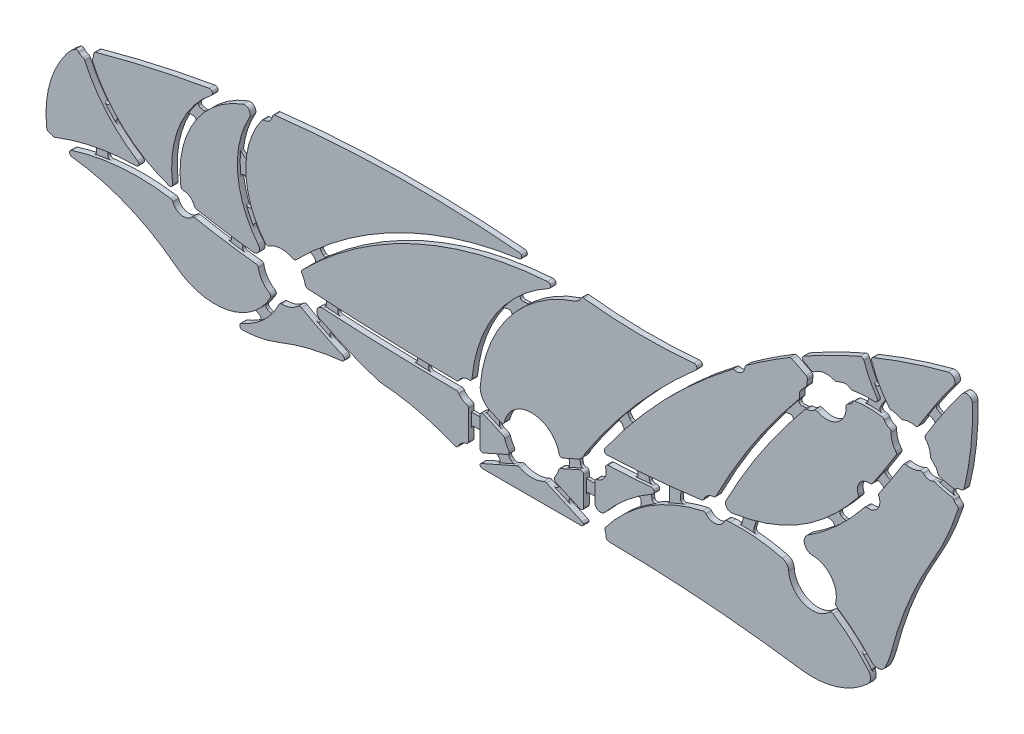
SolidWorks part; units mm, degrees
material "AR-M2"
ref_plane "正面" through (0, 0, 0) normal (0, 0, 1) x (1, 0, 0)
ref_plane "平面" through (0, 0, 0) normal (0, 1, 0) x (1, 0, 0)
ref_plane "右側面" through (0, 0, 0) normal (1, 0, 0) x (0, 0, -1)
sketch "ｽｹｯﾁ1" plane through (0, 0, 0) normal (0, 0, 1) x (1, 0, 0)
  line L1 (-22.5, -10.101) -> (-22.5, 0.101)
  line L2 (-22.5, -10.101) -> (-22.5, 0.101)
  line L3 (22.5, 0.101) -> (22.5, -6.4126)
  line L4 (22.5, 0.101) -> (22.5, -6.4126)
  line L6 (11.119, 1.5832) -> (16.2024, 3.8425)
  line L7 (18.5, -10.042) -> (18.5, 0.042)
  line L8 (8.626, -7.1923) -> (17.0939, -10.9558)
  line L9 (17.0939, 0.9558) -> (10.1663, -2.1231)
  line L10 (18.5, -10.042) -> (18.5, 0.042)
  line L11 (8.626, -7.1923) -> (17.0939, -10.9558)
  line L12 (17.0939, 0.9558) -> (10.1663, -2.1231)
  line L13 (-10.1663, -2.1231) -> (-17.0939, 0.9558)
  line L14 (-17.0939, -10.9558) -> (-8.626, -7.1923)
  line L15 (-18.5, 0.042) -> (-18.5, -10.042)
  line L16 (-10.1663, -2.1231) -> (-17.0939, 0.9558)
  line L17 (-17.0939, -10.9558) -> (-8.626, -7.1923)
  line L18 (-18.5, 0.042) -> (-18.5, -10.042)
  line L19 (-17.5, -16) -> (17.5, -16)
  line L20 (-5.2366, -8.9688) -> (-17.9339, -14.6121)
  line L21 (17.9339, -14.6121) -> (5.2366, -8.9688)
  line L22 (-17.5, -16) -> (17.5, -16)
  line L23 (-5.2366, -8.9688) -> (-17.9339, -14.6121)
  line L24 (17.9339, -14.6121) -> (5.2366, -8.9688)
  line L25 (-14.7807, 3.2107) -> (-11.119, 1.5832)
  line L26 (11.119, 1.5832) -> (16.2024, 3.8425)
  line L27 (-14.7807, 3.2107) -> (-11.119, 1.5832)
  arc A16 (-103.3566, -14.0607) -> (-89.967, -1.5631) centre (-112.8701, 9.5532) ccw
  arc A17 (-89.0603, -0.9998) -> (-89.967, -1.5631) centre (-89.0674, -1.9998) ccw
  arc A18 (-89.0603, -0.9998) -> (-83.2113, 1.2758) centre (-89, 7.5) ccw
  arc A19 (-82.0317, 1.4104) -> (-83.2113, 1.2758) centre (-82.5302, 0.5435) ccw
  arc A20 (-82.0317, 1.4104) -> (-67.3468, -5.898) centre (-13.9413, 119.818) ccw
  arc A21 (-67.6378, -7.8134) -> (-67.3468, -5.898) centre (-67.7378, -6.8184) ccw
  arc A22 (-67.6378, -7.8134) -> (-90.1176, -13.3365) centre (-59.3978, -89.8605) ccw
  arc A23 (-102.9573, -15.9879) -> (-90.1176, -13.3365) centre (-103.9017, 21) ccw
  arc A24 (-103.3566, -14.0607) -> (-102.9573, -15.9879) centre (-102.9829, -14.9883) ccw
  arc A25 (-103.3566, -14.0607) -> (-89.967, -1.5631) centre (-112.8701, 9.5532) ccw
  arc A26 (-89.0603, -0.9998) -> (-89.967, -1.5631) centre (-89.0674, -1.9998) ccw
  arc A27 (-89.0603, -0.9998) -> (-83.2113, 1.2758) centre (-89, 7.5) ccw
  arc A28 (-82.0317, 1.4104) -> (-83.2113, 1.2758) centre (-82.5302, 0.5435) ccw
  arc A29 (-82.0317, 1.4104) -> (-67.3468, -5.898) centre (-13.9413, 119.818) ccw
  arc A30 (-67.6378, -7.8134) -> (-67.3468, -5.898) centre (-67.7378, -6.8184) ccw
  arc A31 (-67.6378, -7.8134) -> (-90.1176, -13.3365) centre (-59.3978, -89.8605) ccw
  arc A32 (-102.9573, -15.9879) -> (-90.1176, -13.3365) centre (-103.9017, 21) ccw
  arc A33 (-103.3566, -14.0607) -> (-102.9573, -15.9879) centre (-102.9829, -14.9883) ccw
  arc A35 (-114.85, 52.6669) -> (-155.2686, 43.5545) centre (-42.29, -363.3692) ccw
  arc A36 (-114.0595, 50.8962) -> (-114.85, 52.6669) centre (-114.6782, 51.6818) ccw
  arc A37 (-114.0595, 50.8962) -> (-127.9008, 16.5808) centre (-91.0356, 21.6602) ccw
  arc A38 (-126.7209, -8.1253) -> (-163.7257, 7.0322) centre (-172, -65.9175) ccw
  arc A39 (-163.9203, 8.9775) -> (-163.7257, 7.0322) centre (-163.613, 8.0259) ccw
  arc A40 (-128.5572, 11.8079) -> (-163.9203, 8.9775) centre (-140.2604, -64.3004) ccw
  arc A41 (-127.7673, 11.1556) -> (-128.5572, 11.8079) centre (-128.7091, 10.8195) ccw
  arc A42 (-127.7673, 11.1556) -> (-121.0036, 9.8502) centre (-124, 12.5) ccw
  arc A43 (-120.0633, 10.1693) -> (-121.0036, 9.8502) centre (-120.2545, 9.1877) ccw
  arc A44 (-120.0633, 10.1693) -> (-98.2474, 6.8503) centre (-69.0994, 271.8045) ccw
  arc A45 (-97.3718, 6.0294) -> (-98.2474, 6.8503) centre (-98.3567, 5.8563) ccw
  arc A46 (-97.3718, 6.0294) -> (-93.4427, 0.2535) centre (-89, 7.5) ccw
  arc A47 (-93.0844, -1.0722) -> (-93.4427, 0.2535) centre (-93.9654, -0.5991) ccw
  arc A48 (-126.7209, -8.1253) -> (-93.0844, -1.0722) centre (-112.8701, 9.5532) ccw
  arc A49 (-126.7209, -8.1253) -> (-163.7257, 7.0322) centre (-172, -65.9175) ccw
  arc A50 (-163.9203, 8.9775) -> (-163.7257, 7.0322) centre (-163.613, 8.0259) ccw
  arc A51 (-128.5572, 11.8079) -> (-163.9203, 8.9775) centre (-140.2604, -64.3004) ccw
  arc A52 (-127.7673, 11.1556) -> (-128.5572, 11.8079) centre (-128.7091, 10.8195) ccw
  arc A53 (-127.7673, 11.1556) -> (-121.0036, 9.8502) centre (-124, 12.5) ccw
  arc A54 (-120.0633, 10.1693) -> (-121.0036, 9.8502) centre (-120.2545, 9.1877) ccw
  arc A55 (-120.0633, 10.1693) -> (-98.2474, 6.8503) centre (-69.0994, 271.8045) ccw
  arc A56 (-97.3718, 6.0294) -> (-98.2474, 6.8503) centre (-98.3567, 5.8563) ccw
  arc A57 (-97.3718, 6.0294) -> (-93.4427, 0.2535) centre (-89, 7.5) ccw
  arc A58 (-93.0844, -1.0722) -> (-93.4427, 0.2535) centre (-93.9654, -0.5991) ccw
  arc A59 (-126.7209, -8.1253) -> (-93.0844, -1.0722) centre (-112.8701, 9.5532) ccw
  arc A60 (-129.2172, 15.4989) -> (-127.9008, 16.5808) centre (-128.8914, 16.4443) ccw
  arc A61 (-156.4002, 40.1644) -> (-129.2172, 15.4989) centre (-114.0417, 59.5347) ccw
  arc A62 (-156.3681, 41.0602) -> (-156.4002, 40.1644) centre (-155.4908, 40.5803) ccw
  arc A63 (-156.3681, 41.0602) -> (-156.0008, 42.5682) centre (-159, 42.5) ccw
  arc A64 (-155.2686, 43.5545) -> (-156.0008, 42.5682) centre (-155.001, 42.5909) ccw
  arc A65 (-114.85, 52.6669) -> (-155.2686, 43.5545) centre (-42.29, -363.3692) ccw
  arc A66 (-114.0595, 50.8962) -> (-114.85, 52.6669) centre (-114.6782, 51.6818) ccw
  arc A67 (-114.0595, 50.8962) -> (-127.9008, 16.5808) centre (-91.0356, 21.6602) ccw
  arc A68 (-129.2172, 15.4989) -> (-127.9008, 16.5808) centre (-128.8914, 16.4443) ccw
  arc A69 (-156.4002, 40.1644) -> (-129.2172, 15.4989) centre (-114.0417, 59.5347) ccw
  arc A70 (-156.3681, 41.0602) -> (-156.4002, 40.1644) centre (-155.4908, 40.5803) ccw
  arc A71 (-156.3681, 41.0602) -> (-156.0008, 42.5682) centre (-159, 42.5) ccw
  arc A72 (-155.2686, 43.5545) -> (-156.0008, 42.5682) centre (-155.001, 42.5909) ccw
  arc A73 (-100.5051, 50.879) -> (-97.4246, 13.2154) centre (-71.0713, 34.3286) ccw
  arc A74 (-99.214, 9.978) -> (-97.4246, 13.2154) centre (-98.9855, 11.9649) ccw
  arc A75 (-4.471, 57.2503) -> (-91.4838, 56.0721) centre (-42.29, -363.3692) ccw
  arc A76 (-140.9263, 15.6997) -> (-169.717, 10.0822) centre (-140.2604, -64.3004) ccw
  arc A77 (-170.5639, 10.1339) -> (-169.717, 10.0822) centre (-170.0852, 11.0119) ccw
  arc A78 (-170.5639, 10.1339) -> (-171.786, 10.4924) centre (-172, 7.5) ccw
  arc A79 (-172.7066, 11.3632) -> (-171.786, 10.4924) centre (-171.7146, 11.4898) ccw
  arc A80 (-165.6353, 37.9447) -> (-172.7066, 11.3632) centre (-136.5587, 15.9784) ccw
  arc A81 (-162.6526, 40.7855) -> (-165.6353, 37.9447) centre (-155.4945, 30.2837) ccw
  arc A82 (-161.317, 40.5944) -> (-162.6526, 40.7855) centre (-162.0894, 39.9592) ccw
  arc A83 (-161.317, 40.5944) -> (-159.8316, 39.6176) centre (-159, 42.5) ccw
  arc A84 (-159.198, 39.0695) -> (-159.8316, 39.6176) centre (-160.1088, 38.6568) ccw
  arc A85 (-159.198, 39.0695) -> (-140.4029, 17.5466) centre (-114.0417, 59.5347) ccw
  arc A86 (-140.9263, 15.6997) -> (-140.4029, 17.5466) centre (-140.9346, 16.6997) ccw
  arc A87 (-140.9263, 15.6997) -> (-169.717, 10.0822) centre (-140.2604, -64.3004) ccw
  arc A88 (-170.5639, 10.1339) -> (-169.717, 10.0822) centre (-170.0852, 11.0119) ccw
  arc A89 (-170.5639, 10.1339) -> (-171.786, 10.4924) centre (-172, 7.5) ccw
  arc A90 (-172.7066, 11.3632) -> (-171.786, 10.4924) centre (-171.7146, 11.4898) ccw
  arc A91 (-165.6353, 37.9447) -> (-172.7066, 11.3632) centre (-136.5587, 15.9784) ccw
  arc A92 (-162.6526, 40.7855) -> (-165.6353, 37.9447) centre (-155.4945, 30.2837) ccw
  arc A93 (-161.317, 40.5944) -> (-162.6526, 40.7855) centre (-162.0894, 39.9592) ccw
  arc A94 (-161.317, 40.5944) -> (-159.8316, 39.6176) centre (-159, 42.5) ccw
  arc A95 (-159.198, 39.0695) -> (-159.8316, 39.6176) centre (-160.1088, 38.6568) ccw
  arc A96 (-159.198, 39.0695) -> (-140.4029, 17.5466) centre (-114.0417, 59.5347) ccw
  arc A97 (-140.9263, 15.6997) -> (-140.4029, 17.5466) centre (-140.9346, 16.6997) ccw
  arc A98 (-4.4224, 55.2639) -> (-4.471, 57.2503) centre (-4.5606, 56.2543) ccw
  arc A99 (-4.4224, 55.2639) -> (-83.9236, 15.238) centre (14.6672, -81.6202) ccw
  arc A100 (-85.0963, 15.0506) -> (-83.9236, 15.238) centre (-84.637, 15.9389) ccw
  arc A101 (-85.0963, 15.0506) -> (-93.5868, 14.6562) centre (-89, 7.5) ccw
  arc A102 (-94.9009, 14.8656) -> (-93.5868, 14.6562) centre (-94.1264, 15.4981) ccw
  arc A103 (-96.1287, 52.1831) -> (-94.9009, 14.8656) centre (-71.0713, 34.3286) ccw
  arc A104 (-95.319, 52.6028) -> (-96.1287, 52.1831) centre (-95.3143, 51.6028) ccw
  arc A105 (-95.319, 52.6028) -> (-92.3587, 55.2099) centre (-95.3328, 55.6027) ccw
  arc A106 (-91.4838, 56.0721) -> (-92.3587, 55.2099) centre (-91.3673, 55.0789) ccw
  arc A107 (-4.471, 57.2503) -> (-91.4838, 56.0721) centre (-42.29, -363.3692) ccw
  arc A108 (-4.4224, 55.2639) -> (-4.471, 57.2503) centre (-4.5606, 56.2543) ccw
  arc A109 (-4.4224, 55.2639) -> (-83.9236, 15.238) centre (14.6672, -81.6202) ccw
  arc A110 (-85.0963, 15.0506) -> (-83.9236, 15.238) centre (-84.637, 15.9389) ccw
  arc A111 (-85.0963, 15.0506) -> (-93.5868, 14.6562) centre (-89, 7.5) ccw
  arc A112 (-94.9009, 14.8656) -> (-93.5868, 14.6562) centre (-94.1264, 15.4981) ccw
  arc A113 (-96.1287, 52.1831) -> (-94.9009, 14.8656) centre (-71.0713, 34.3286) ccw
  arc A114 (-95.319, 52.6028) -> (-96.1287, 52.1831) centre (-95.3143, 51.6028) ccw
  arc A115 (-95.319, 52.6028) -> (-92.3587, 55.2099) centre (-95.3328, 55.6027) ccw
  arc A116 (-91.4838, 56.0721) -> (-92.3587, 55.2099) centre (-91.3673, 55.0789) ccw
  arc A117 (-22.314, 8.9957) -> (-25.9592, 7.0085) centre (-22.5, 5) ccw
  arc A118 (-26.8289, 6.5106) -> (-25.9592, 7.0085) centre (-26.824, 7.5106) ccw
  arc A119 (-79.7472, 8.3552) -> (-26.8289, 6.5106) centre (-22.5, 890.7) ccw
  arc A120 (-80.6633, 9.158) -> (-79.7472, 8.3552) centre (-79.6825, 9.3531) ccw
  arc A121 (-80.6633, 9.158) -> (-81.8017, 12.0204) centre (-89, 7.5) ccw
  arc A122 (-81.6673, 13.2539) -> (-81.8017, 12.0204) centre (-80.9548, 12.5522) ccw
  arc A123 (5.6096, 53.2849) -> (-81.6673, 13.2539) centre (14.6672, -81.6202) ccw
  arc A124 (6.1525, 51.4076) -> (5.6096, 53.2849) centre (5.6766, 52.2871) ccw
  arc A125 (6.1525, 51.4076) -> (-21.2718, 9.9017) centre (31.2679, 5) ccw
  arc A126 (-22.314, 8.9957) -> (-21.2718, 9.9017) centre (-22.2675, 9.9946) ccw
  arc A127 (-22.314, 8.9957) -> (-25.9592, 7.0085) centre (-22.5, 5) ccw
  arc A128 (-26.8289, 6.5106) -> (-25.9592, 7.0085) centre (-26.824, 7.5106) ccw
  arc A129 (-79.7472, 8.3552) -> (-26.8289, 6.5106) centre (-22.5, 890.7) ccw
  arc A130 (-80.6633, 9.158) -> (-79.7472, 8.3552) centre (-79.6825, 9.3531) ccw
  arc A131 (-80.6633, 9.158) -> (-81.8017, 12.0204) centre (-89, 7.5) ccw
  arc A132 (-81.6673, 13.2539) -> (-81.8017, 12.0204) centre (-80.9548, 12.5522) ccw
  arc A133 (5.6096, 53.2849) -> (-81.6673, 13.2539) centre (14.6672, -81.6202) ccw
  arc A134 (6.1525, 51.4076) -> (5.6096, 53.2849) centre (5.6766, 52.2871) ccw
  arc A135 (6.1525, 51.4076) -> (-21.2718, 9.9017) centre (31.2679, 5) ccw
  arc A136 (-22.314, 8.9957) -> (-21.2718, 9.9017) centre (-22.2675, 9.9946) ccw
  arc A137 (-119.4498, 13.1062) -> (-99.214, 9.978) centre (-69.0994, 271.8045) ccw
  arc A138 (-27.4366, -13.8466) -> (-54.0639, -7.5734) centre (-59.3978, -89.8605) ccw
  arc A139 (-54.3014, -7.5287) -> (-54.0639, -7.5734) centre (-53.9993, -6.5755) ccw
  arc A140 (-75.487, 1.2505) -> (-54.3014, -7.5287) centre (-13.9413, 119.818) ccw
  arc A141 (-74.4485, 5.0222) -> (-75.487, 1.2505) centre (-74.5656, 3.0256) ccw
  arc A142 (-74.4485, 5.0222) -> (-26.8313, 3.5106) centre (-22.5, 890.7) ccw
  arc A143 (-25.969, 3.0085) -> (-26.8313, 3.5106) centre (-26.8362, 2.5106) ccw
  arc A144 (-25.969, 3.0085) -> (-23.3, 1.0808) centre (-22.5, 5) ccw
  arc A145 (-22.5, 0.101) -> (-23.3, 1.0808) centre (-23.5, 0.101) ccw
  arc A146 (-23.3, -11.0808) -> (-22.5, -10.101) centre (-23.5, -10.101) ccw
  arc A147 (-23.3, -11.0808) -> (-26.1392, -13.3399) centre (-22.5, -15) ccw
  arc A148 (-27.4366, -13.8466) -> (-26.1392, -13.3399) centre (-27.049, -12.9248) ccw
  arc A149 (-27.4366, -13.8466) -> (-54.0639, -7.5734) centre (-59.3978, -89.8605) ccw
  arc A150 (-54.3014, -7.5287) -> (-54.0639, -7.5734) centre (-53.9993, -6.5755) ccw
  arc A151 (-75.487, 1.2505) -> (-54.3014, -7.5287) centre (-13.9413, 119.818) ccw
  arc A152 (-74.4485, 5.0222) -> (-75.487, 1.2505) centre (-74.5656, 3.0256) ccw
  arc A153 (-74.4485, 5.0222) -> (-26.8313, 3.5106) centre (-22.5, 890.7) ccw
  arc A154 (-25.969, 3.0085) -> (-26.8313, 3.5106) centre (-26.8362, 2.5106) ccw
  arc A155 (-25.969, 3.0085) -> (-23.3, 1.0808) centre (-22.5, 5) ccw
  arc A156 (-22.5, 0.101) -> (-23.3, 1.0808) centre (-23.5, 0.101) ccw
  arc A157 (-23.3, -11.0808) -> (-22.5, -10.101) centre (-23.5, -10.101) ccw
  arc A158 (-23.3, -11.0808) -> (-26.1392, -13.3399) centre (-22.5, -15) ccw
  arc A159 (-27.4366, -13.8466) -> (-26.1392, -13.3399) centre (-27.049, -12.9248) ccw
  arc A160 (-120.207, 13.7702) -> (-119.4498, 13.1062) centre (-119.2588, 14.0878) ccw
  arc A161 (-120.207, 13.7702) -> (-123.99, 16.5) centre (-124, 12.5) ccw
  arc A162 (-124.9796, 17.3747) -> (-123.99, 16.5) centre (-123.9875, 17.5) ccw
  arc A163 (-102.9446, 53.7342) -> (-124.9796, 17.3747) centre (-91.0356, 21.6602) ccw
  arc A164 (-100.5051, 50.879) -> (-102.9446, 53.7342) centre (-102.2484, 51.8592) ccw
  arc A165 (-100.5051, 50.879) -> (-97.4246, 13.2154) centre (-71.0713, 34.3286) ccw
  arc A166 (-99.214, 9.978) -> (-97.4246, 13.2154) centre (-98.9855, 11.9649) ccw
  arc A167 (-119.4498, 13.1062) -> (-99.214, 9.978) centre (-69.0994, 271.8045) ccw
  arc A168 (-120.207, 13.7702) -> (-119.4498, 13.1062) centre (-119.2588, 14.0878) ccw
  arc A169 (-120.207, 13.7702) -> (-123.99, 16.5) centre (-124, 12.5) ccw
  arc A170 (-124.9796, 17.3747) -> (-123.99, 16.5) centre (-123.9875, 17.5) ccw
  arc A171 (-102.9446, 53.7342) -> (-124.9796, 17.3747) centre (-91.0356, 21.6602) ccw
  arc A172 (-100.5051, 50.879) -> (-102.9446, 53.7342) centre (-102.2484, 51.8592) ccw
  arc A180 (17.0939, -10.9558) -> (18.5, -10.042) centre (17.5, -10.042) ccw
  arc A181 (8.2111, -5.7077) -> (8.626, -7.1923) centre (9.0322, -6.2785) ccw
  arc A182 (22.5, -6.4126) -> (26.0294, -7.7013) centre (24.5, -6.4126) ccw
  arc A183 (23.3, 1.0808) -> (22.5, 0.101) centre (23.5, 0.101) ccw
  arc A184 (23.3, 1.0808) -> (26.3403, 6.1191) centre (22.5, 5) ccw
  arc A185 (27.2601, 7.398) -> (26.3403, 6.1191) centre (27.3003, 6.3988) ccw
  arc A186 (27.2601, 7.398) -> (42.5161, 8.3479) centre (13.2682, 355.1295) ccw
  arc A187 (43.0938, 6.4818) -> (42.5161, 8.3479) centre (42.6001, 7.3514) ccw
  arc A188 (107.7452, 73.9205) -> (100.6016, 72.9268) centre (105, 67.4812) ccw
  arc A189 (99.4771, 72.8365) -> (100.6016, 72.9268) centre (99.9733, 73.7047) ccw
  arc A190 (99.4771, 72.8365) -> (96.9768, 74.198) centre (65, 12.5) ccw
  arc A191 (96.9469, 75.9576) -> (96.9768, 74.198) centre (97.4369, 75.0859) ccw
  arc A192 (116.993, 85.9037) -> (96.9469, 75.9576) centre (203.2901, -113.1988) ccw
  arc A193 (118.3344, 85.3171) -> (116.993, 85.9037) centre (117.3907, 84.9862) ccw
  arc A194 (118.3344, 85.3171) -> (122.9876, 76.0572) centre (156.5, 98.6967) ccw
  arc A195 (122.0896, 74.4999) -> (122.9876, 76.0572) centre (122.1589, 75.4974) ccw
  arc A196 (122.0896, 74.4999) -> (114.3306, 74.0344) centre (120, 44.4324) ccw
  arc A197 (113.5331, 74.2236) -> (114.3306, 74.0344) centre (114.1425, 75.0165) ccw
  arc A198 (113.5331, 74.2236) -> (110.8362, 74.7163) centre (111.7051, 71.8449) ccw
  arc A199 (110.8362, 74.7163) -> (108.5008, 73.9088) centre (120, 44.4324) ccw
  arc A200 (107.7452, 73.9205) -> (108.5008, 73.9088) centre (108.1373, 74.8404) ccw
  arc A201 (107.7452, 73.9205) -> (100.6016, 72.9268) centre (105, 67.4812) ccw
  arc A202 (99.4771, 72.8365) -> (100.6016, 72.9268) centre (99.9733, 73.7047) ccw
  arc A203 (99.4771, 72.8365) -> (96.9768, 74.198) centre (65, 12.5) ccw
  arc A204 (96.9469, 75.9576) -> (96.9768, 74.198) centre (97.4369, 75.0859) ccw
  arc A205 (116.993, 85.9037) -> (96.9469, 75.9576) centre (203.2901, -113.1988) ccw
  arc A206 (118.3344, 85.3171) -> (116.993, 85.9037) centre (117.3907, 84.9862) ccw
  arc A207 (118.3344, 85.3171) -> (122.9876, 76.0572) centre (156.5, 98.6967) ccw
  arc A208 (122.0896, 74.4999) -> (122.9876, 76.0572) centre (122.1589, 75.4974) ccw
  arc A209 (122.0896, 74.4999) -> (114.3306, 74.0344) centre (120, 44.4324) ccw
  arc A210 (113.5331, 74.2236) -> (114.3306, 74.0344) centre (114.1425, 75.0165) ccw
  arc A211 (113.5331, 74.2236) -> (110.8362, 74.7163) centre (111.7051, 71.8449) ccw
  arc A212 (110.8362, 74.7163) -> (108.5008, 73.9088) centre (120, 44.4324) ccw
  arc A213 (107.7452, 73.9205) -> (108.5008, 73.9088) centre (108.1373, 74.8404) ccw
  arc A214 (43.0938, 6.4818) -> (26.0294, -7.7013) centre (74.1755, -48.2713) ccw
  arc A215 (22.5, -6.4126) -> (26.0294, -7.7013) centre (24.5, -6.4126) ccw
  arc A216 (23.3, 1.0808) -> (22.5, 0.101) centre (23.5, 0.101) ccw
  arc A217 (23.3, 1.0808) -> (26.3403, 6.1191) centre (22.5, 5) ccw
  arc A218 (89.2736, 9.7568) -> (70.6824, 11.5869) centre (74.1755, -48.2713) ccw
  arc A219 (91.5134, 7.0221) -> (89.2736, 9.7568) centre (88.5182, 6.8535) ccw
  arc A220 (91.5134, 7.0221) -> (106.0705, 1.5503) centre (100, 7.5) ccw
  arc A221 (107.3377, 1.6835) -> (106.0705, 1.5503) centre (106.7847, 0.8503) ccw
  arc A222 (120.0008, -9.6028) -> (107.3377, 1.6835) centre (74.1755, -48.2713) ccw
  arc A223 (119.7512, -13.7341) -> (120.0008, -9.6028) centre (117.708, -11.5375) ccw
  arc A224 (95.9045, -21.2094) -> (119.7512, -13.7341) centre (100, 7.5) ccw
  arc A225 (95.9045, -21.2094) -> (27.4903, -16.024) centre (22.5, -535.7727) ccw
  arc A226 (26.5, -15.0192) -> (27.4903, -16.024) centre (27.4999, -15.024) ccw
  arc A227 (26.5, -15.0192) -> (26.1198, -13.2978) centre (22.5, -15) ccw
  arc A228 (26.225, -12.2719) -> (26.1198, -13.2978) centre (27.0247, -12.8723) ccw
  arc A229 (60.9851, 10.2199) -> (26.225, -12.2719) centre (74.1755, -48.2713) ccw
  arc A230 (61.9641, 9.8955) -> (60.9851, 10.2199) centre (61.2051, 9.2444) ccw
  arc A231 (61.9641, 9.8955) -> (60.9851, 10.2199) centre (61.2051, 9.2444) ccw
  arc A232 (61.9641, 9.8955) -> (68.6424, 10.8468) centre (65, 12.5) ccw
  arc A233 (69.4305, 11.426) -> (70.604, 11.5793) centre (59.3082, 93.4746) ccw
  arc A234 (70.6824, 11.5869) -> (70.604, 11.5793) centre (70.7407, 10.5886) ccw
  arc A235 (89.2736, 9.7568) -> (70.6824, 11.5869) centre (74.1755, -48.2713) ccw
  arc A236 (91.5134, 7.0221) -> (89.2736, 9.7568) centre (88.5182, 6.8535) ccw
  arc A237 (91.5134, 7.0221) -> (106.0705, 1.5503) centre (100, 7.5) ccw
  arc A238 (107.3377, 1.6835) -> (106.0705, 1.5503) centre (106.7847, 0.8503) ccw
  arc A239 (120.0008, -9.6028) -> (107.3377, 1.6835) centre (74.1755, -48.2713) ccw
  arc A240 (119.7512, -13.7341) -> (120.0008, -9.6028) centre (117.708, -11.5375) ccw
  arc A241 (95.9045, -21.2094) -> (119.7512, -13.7341) centre (100, 7.5) ccw
  arc A242 (95.9045, -21.2094) -> (27.4903, -16.024) centre (22.5, -535.7727) ccw
  arc A243 (26.5, -15.0192) -> (27.4903, -16.024) centre (27.4999, -15.024) ccw
  arc A244 (26.5, -15.0192) -> (26.1198, -13.2978) centre (22.5, -15) ccw
  arc A245 (26.225, -12.2719) -> (26.1198, -13.2978) centre (27.0247, -12.8723) ccw
  arc A246 (60.9851, 10.2199) -> (26.225, -12.2719) centre (74.1755, -48.2713) ccw
  arc A247 (61.9641, 9.8955) -> (68.6424, 10.8468) centre (65, 12.5) ccw
  arc A248 (69.4305, 11.426) -> (68.6424, 10.8468) centre (69.553, 10.4335) ccw
  arc A249 (69.4305, 11.426) -> (68.6424, 10.8468) centre (69.553, 10.4335) ccw
  arc A250 (69.4305, 11.426) -> (70.604, 11.5793) centre (59.3082, 93.4746) ccw
  arc A251 (70.6824, 11.5869) -> (70.604, 11.5793) centre (70.7407, 10.5886) ccw
  arc A252 (27.2601, 7.398) -> (26.3403, 6.1191) centre (27.3003, 6.3988) ccw
  arc A253 (27.2601, 7.398) -> (42.5161, 8.3479) centre (13.2682, 355.1295) ccw
  arc A254 (71.3431, 59.0772) -> (26.022, 11.9612) centre (203.2901, -113.1988) ccw
  arc A255 (72.1979, 59.2524) -> (71.3431, 59.0772) centre (71.9512, 58.2833) ccw
  arc A256 (72.1979, 59.2524) -> (71.3431, 59.0772) centre (71.9512, 58.2833) ccw
  arc A257 (72.1979, 59.2524) -> (75.9352, 62.0305) centre (72.938, 62.1596) ccw
  arc A258 (72.1979, 59.2524) -> (75.9352, 62.0305) centre (72.938, 62.1596) ccw
  arc A259 (92.6465, 72.9722) -> (91.7165, 72.9204) centre (92.2307, 72.0627) ccw
  arc A260 (97.7506, 70.3671) -> (92.6465, 72.9722) centre (65, 12.5) ccw
  arc A261 (98.2258, 69.2449) -> (97.7506, 70.3671) centre (97.2581, 69.4969) ccw
  arc A262 (98.2258, 69.2449) -> (98.0007, 67.5789) centre (105, 67.4812) ccw
  arc A263 (97.7054, 66.8832) -> (98.0007, 67.5789) centre (97.0008, 67.5928) ccw
  arc A264 (97.7054, 66.8832) -> (96.0213, 65.0748) centre (120, 44.4324) ccw
  arc A265 (96.0213, 65.0748) -> (95.3497, 62.5466) centre (98.2949, 63.1176) ccw
  arc A266 (95.1344, 61.7139) -> (95.3497, 62.5466) centre (94.368, 62.3562) ccw
  arc A267 (95.1344, 61.7139) -> (65.5834, 17.0366) centre (276.8279, -90.5756) ccw
  arc A268 (76.3493, 62.7985) -> (75.9352, 62.0305) centre (76.9343, 61.9874) ccw
  arc A269 (76.3493, 62.7985) -> (75.9352, 62.0305) centre (76.9343, 61.9874) ccw
  arc A270 (91.7165, 72.9204) -> (76.3493, 62.7985) centre (203.2901, -113.1988) ccw
  arc A271 (26.8783, 10.3852) -> (60.4936, 13.364) centre (13.2682, 355.1295) ccw
  arc A272 (26.022, 11.9612) -> (26.8783, 10.3852) centre (26.8389, 11.3844) ccw
  arc A273 (71.3431, 59.0772) -> (26.022, 11.9612) centre (203.2901, -113.1988) ccw
  arc A274 (91.7165, 72.9204) -> (76.3493, 62.7985) centre (203.2901, -113.1988) ccw
  arc A275 (64.7539, 16.4924) -> (65.5834, 17.0366) centre (64.6924, 17.4905) ccw
  arc A276 (64.7539, 16.4924) -> (65.5834, 17.0366) centre (64.6924, 17.4905) ccw
  arc A277 (64.7539, 16.4924) -> (61.2853, 13.9837) centre (65, 12.5) ccw
  arc A278 (92.6465, 72.9722) -> (91.7165, 72.9204) centre (92.2307, 72.0627) ccw
  arc A279 (97.7506, 70.3671) -> (92.6465, 72.9722) centre (65, 12.5) ccw
  arc A280 (98.2258, 69.2449) -> (97.7506, 70.3671) centre (97.2581, 69.4969) ccw
  arc A281 (98.2258, 69.2449) -> (98.0007, 67.5789) centre (105, 67.4812) ccw
  arc A282 (97.7054, 66.8832) -> (98.0007, 67.5789) centre (97.0008, 67.5928) ccw
  arc A283 (97.7054, 66.8832) -> (96.0213, 65.0748) centre (120, 44.4324) ccw
  arc A284 (96.0213, 65.0748) -> (95.3497, 62.5466) centre (98.2949, 63.1176) ccw
  arc A285 (95.1344, 61.7139) -> (95.3497, 62.5466) centre (94.368, 62.3562) ccw
  arc A286 (95.1344, 61.7139) -> (65.5834, 17.0366) centre (276.8279, -90.5756) ccw
  arc A287 (64.7539, 16.4924) -> (61.2853, 13.9837) centre (65, 12.5) ccw
  arc A288 (60.4936, 13.364) -> (61.2853, 13.9837) centre (60.3567, 14.3546) ccw
  arc A289 (60.4936, 13.364) -> (61.2853, 13.9837) centre (60.3567, 14.3546) ccw
  arc A290 (26.8783, 10.3852) -> (60.4936, 13.364) centre (13.2682, 355.1295) ccw
  arc A291 (26.022, 11.9612) -> (26.8783, 10.3852) centre (26.8389, 11.3844) ccw
  arc A292 (43.0938, 6.4818) -> (42.5161, 8.3479) centre (42.6001, 7.3514) ccw
  arc A293 (43.0938, 6.4818) -> (26.0294, -7.7013) centre (74.1755, -48.2713) ccw
  arc A294 (8.2111, -5.7077) -> (9.6113, -2.7608) centre (0, 0) ccw
  arc A295 (10.1663, -2.1231) -> (9.6113, -2.7608) centre (10.5725, -3.0369) ccw
  arc A296 (18.5, 0.042) -> (17.0939, 0.9558) centre (17.5, 0.042) ccw
  arc A297 (148.2331, 96.7006) -> (121.6343, 87.8518) centre (203.2901, -113.1988) ccw
  arc A298 (150.3263, 93.5472) -> (148.2331, 96.7006) centre (148.7406, 94.766) ccw
  arc A302 (136.5911, 74.298) -> (137.6701, 74.7478) centre (136.8184, 75.2718) ccw
  arc A303 (136.5911, 74.298) -> (132.2548, 73.9205) centre (135, 67.4812) ccw
  arc A304 (131.4992, 73.9088) -> (132.2548, 73.9205) centre (131.8627, 74.8404) ccw
  arc A305 (131.4992, 73.9088) -> (129.1638, 74.7163) centre (120, 44.4324) ccw
  arc A306 (129.1638, 74.7163) -> (128.1602, 74.8418) centre (128.2949, 71.8449) ccw
  arc A307 (127.3364, 75.2137) -> (128.1602, 74.8418) centre (128.1152, 75.8408) ccw
  arc A308 (69.2577, 17.6177) -> (71.3333, 14.7162) centre (71.0313, 16.6932) ccw
  arc A309 (97.4124, 59.7615) -> (69.2577, 17.6177) centre (276.8279, -90.5756) ccw
  arc A310 (98.2079, 60.1189) -> (97.4124, 59.7615) centre (98.1789, 59.1193) ccw
  arc A311 (98.2079, 60.1189) -> (100.5079, 61.0921) centre (98.2949, 63.1176) ccw
  arc A312 (101.7149, 61.3) -> (100.5079, 61.0921) centre (101.2456, 60.4169) ccw
  arc A313 (101.7149, 61.3) -> (111.9821, 67.9818) centre (105, 67.4812) ccw
  arc A314 (112.6609, 69.0012) -> (111.9821, 67.9818) centre (112.9795, 68.0533) ccw
  arc A315 (112.6609, 69.0012) -> (114.4231, 70.575) centre (111.7051, 71.8449) ccw
  arc A316 (115.1504, 71.1356) -> (114.4231, 70.575) centre (115.3291, 70.1517) ccw
  arc A317 (124.8496, 71.1356) -> (115.1504, 71.1356) centre (120, 44.4324) ccw
  arc A318 (125.5769, 70.575) -> (124.8496, 71.1356) centre (124.6709, 70.1517) ccw
  arc A319 (125.5769, 70.575) -> (127.3391, 69.0012) centre (128.2949, 71.8449) ccw
  arc A320 (128.0179, 67.9818) -> (127.3391, 69.0012) centre (127.0205, 68.0533) ccw
  arc A321 (128.0179, 67.9818) -> (129.6706, 62.9428) centre (135, 67.4812) ccw
  arc A322 (129.7605, 61.7697) -> (129.6706, 62.9428) centre (128.9093, 62.2944) ccw
  arc A323 (120.4118, 48.4111) -> (121.3328, 48.8307) centre (120.5147, 49.4058) ccw
  arc A324 (120.4118, 48.4111) -> (116.299, 42.915) centre (120, 44.4324) ccw
  arc A325 (116.1539, 41.9101) -> (116.299, 42.915) centre (115.3737, 42.5356) ccw
  arc A326 (69.2577, 17.6177) -> (71.3333, 14.7162) centre (71.0313, 16.6932) ccw
  arc A327 (97.4124, 59.7615) -> (69.2577, 17.6177) centre (276.8279, -90.5756) ccw
  arc A328 (98.2079, 60.1189) -> (97.4124, 59.7615) centre (98.1789, 59.1193) ccw
  arc A329 (98.2079, 60.1189) -> (100.5079, 61.0921) centre (98.2949, 63.1176) ccw
  arc A330 (101.7149, 61.3) -> (100.5079, 61.0921) centre (101.2456, 60.4169) ccw
  arc A331 (101.7149, 61.3) -> (111.9821, 67.9818) centre (105, 67.4812) ccw
  arc A332 (112.6609, 69.0012) -> (111.9821, 67.9818) centre (112.9795, 68.0533) ccw
  arc A333 (112.6609, 69.0012) -> (114.4231, 70.575) centre (111.7051, 71.8449) ccw
  arc A334 (115.1504, 71.1356) -> (114.4231, 70.575) centre (115.3291, 70.1517) ccw
  arc A335 (124.8496, 71.1356) -> (115.1504, 71.1356) centre (120, 44.4324) ccw
  arc A336 (125.5769, 70.575) -> (124.8496, 71.1356) centre (124.6709, 70.1517) ccw
  arc A337 (125.5769, 70.575) -> (127.3391, 69.0012) centre (128.2949, 71.8449) ccw
  arc A338 (128.0179, 67.9818) -> (127.3391, 69.0012) centre (127.0205, 68.0533) ccw
  arc A339 (128.0179, 67.9818) -> (129.6706, 62.9428) centre (135, 67.4812) ccw
  arc A340 (129.7605, 61.7697) -> (129.6706, 62.9428) centre (128.9093, 62.2944) ccw
  arc A341 (120.4118, 48.4111) -> (121.3328, 48.8307) centre (120.5147, 49.4058) ccw
  arc A342 (120.4118, 48.4111) -> (116.299, 42.915) centre (120, 44.4324) ccw
  arc A343 (116.1539, 41.9101) -> (116.299, 42.915) centre (115.3737, 42.5356) ccw
  arc A344 (121.0642, 86.6023) -> (127.3364, 75.2137) centre (156.5, 98.6967) ccw
  arc A345 (121.6343, 87.8518) -> (121.0642, 86.6023) centre (122.0106, 86.9253) ccw
  arc A346 (148.2331, 96.7006) -> (121.6343, 87.8518) centre (203.2901, -113.1988) ccw
  arc A347 (150.3263, 93.5472) -> (148.2331, 96.7006) centre (148.7406, 94.766) ccw
  arc A348 (136.5911, 74.298) -> (137.6701, 74.7478) centre (136.8184, 75.2718) ccw
  arc A349 (136.5911, 74.298) -> (132.2548, 73.9205) centre (135, 67.4812) ccw
  arc A350 (131.4992, 73.9088) -> (132.2548, 73.9205) centre (131.8627, 74.8404) ccw
  arc A351 (131.4992, 73.9088) -> (129.1638, 74.7163) centre (120, 44.4324) ccw
  arc A352 (129.1638, 74.7163) -> (128.1602, 74.8418) centre (128.2949, 71.8449) ccw
  arc A353 (127.3364, 75.2137) -> (128.1602, 74.8418) centre (128.1152, 75.8408) ccw
  arc A354 (121.0642, 86.6023) -> (127.3364, 75.2137) centre (156.5, 98.6967) ccw
  arc A355 (121.6343, 87.8518) -> (121.0642, 86.6023) centre (122.0106, 86.9253) ccw
  arc A356 (17.0939, -10.9558) -> (18.5, -10.042) centre (17.5, -10.042) ccw
  arc A357 (8.2111, -5.7077) -> (8.626, -7.1923) centre (9.0322, -6.2785) ccw
  arc A358 (8.2111, -5.7077) -> (9.6113, -2.7608) centre (0, 0) ccw
  arc A359 (10.1663, -2.1231) -> (9.6113, -2.7608) centre (10.5725, -3.0369) ccw
  arc A360 (18.5, 0.042) -> (17.0939, 0.9558) centre (17.5, 0.042) ccw
  arc A361 (-9.6113, -2.7608) -> (-10.1663, -2.1231) centre (-10.5725, -3.0369) ccw
  arc A362 (-9.6113, -2.7608) -> (-8.2111, -5.7077) centre (0, 0) ccw
  arc A363 (-8.626, -7.1923) -> (-8.2111, -5.7077) centre (-9.0322, -6.2785) ccw
  arc A364 (-18.5, -10.042) -> (-17.0939, -10.9558) centre (-17.5, -10.042) ccw
  arc A365 (-17.0939, 0.9558) -> (-18.5, 0.042) centre (-17.5, 0.042) ccw
  arc A366 (-9.6113, -2.7608) -> (-10.1663, -2.1231) centre (-10.5725, -3.0369) ccw
  arc A367 (-9.6113, -2.7608) -> (-8.2111, -5.7077) centre (0, 0) ccw
  arc A368 (-8.626, -7.1923) -> (-8.2111, -5.7077) centre (-9.0322, -6.2785) ccw
  arc A369 (-18.5, -10.042) -> (-17.0939, -10.9558) centre (-17.5, -10.042) ccw
  arc A370 (-17.0939, 0.9558) -> (-18.5, 0.042) centre (-17.5, 0.042) ccw
  arc A373 (18.4772, -15.2121) -> (17.9339, -14.6121) centre (17.5277, -15.5259) ccw
  arc A374 (17.5, -16) -> (18.4772, -15.2121) centre (17.5, -15) ccw
  arc A375 (-18.4772, -15.2121) -> (-17.5, -16) centre (-17.5, -15) ccw
  arc A376 (-17.9339, -14.6121) -> (-18.4772, -15.2121) centre (-17.5277, -15.5259) ccw
  arc A377 (-4.3913, -8.9842) -> (-5.2366, -8.9688) centre (-4.8304, -9.8827) ccw
  arc A378 (-4.3913, -8.9842) -> (4.3913, -8.9842) centre (0, 0) ccw
  arc A379 (5.2366, -8.9688) -> (4.3913, -8.9842) centre (4.8304, -9.8827) ccw
  arc A380 (18.4772, -15.2121) -> (17.9339, -14.6121) centre (17.5277, -15.5259) ccw
  arc A381 (17.5, -16) -> (18.4772, -15.2121) centre (17.5, -15) ccw
  arc A382 (-18.4772, -15.2121) -> (-17.5, -16) centre (-17.5, -15) ccw
  arc A383 (-17.9339, -14.6121) -> (-18.4772, -15.2121) centre (-17.5277, -15.5259) ccw
  arc A384 (-4.3913, -8.9842) -> (-5.2366, -8.9688) centre (-4.8304, -9.8827) ccw
  arc A385 (-4.3913, -8.9842) -> (4.3913, -8.9842) centre (0, 0) ccw
  arc A386 (5.2366, -8.9688) -> (4.3913, -8.9842) centre (4.8304, -9.8827) ccw
  arc A392 (15.611, 52.2409) -> (17.4557, 53.9822) centre (14.6672, 55.0886) ccw
  arc A393 (18.4998, 54.6068) -> (17.4557, 53.9822) centre (18.3852, 53.6134) ccw
  arc A394 (18.4998, 54.6068) -> (57.7478, 54.1867) centre (40.1338, 242.1889) ccw
  arc A395 (58.4992, 52.4382) -> (57.7478, 54.1867) centre (57.841, 53.1911) ccw
  arc A396 (58.4992, 52.4382) -> (19.152, 7.1889) centre (203.2901, -113.1988) ccw
  arc A397 (19.152, 7.1889) -> (18.7985, 6.5163) centre (22.5, 5) ccw
  arc A398 (16.2024, 3.8425) -> (18.7985, 6.5163) centre (14.1717, 8.4116) ccw
  arc A399 (9.7389, 2.27) -> (11.119, 1.5832) centre (10.7128, 2.4971) ccw
  arc A400 (9.7389, 2.27) -> (-9.7389, 2.27) centre (0, 0) ccw
  arc A401 (-11.119, 1.5832) -> (-9.7389, 2.27) centre (-10.7128, 2.4971) ccw
  arc A402 (-18.3225, 9.1999) -> (-14.7807, 3.2107) centre (-12.3439, 8.6935) ccw
  arc A403 (15.611, 52.2409) -> (-18.3225, 9.1999) centre (31.2679, 5) ccw
  arc A404 (15.611, 52.2409) -> (17.4557, 53.9822) centre (14.6672, 55.0886) ccw
  arc A405 (18.4998, 54.6068) -> (17.4557, 53.9822) centre (18.3852, 53.6134) ccw
  arc A406 (18.4998, 54.6068) -> (57.7478, 54.1867) centre (40.1338, 242.1889) ccw
  arc A407 (58.4992, 52.4382) -> (57.7478, 54.1867) centre (57.841, 53.1911) ccw
  arc A408 (58.4992, 52.4382) -> (19.152, 7.1889) centre (203.2901, -113.1988) ccw
  arc A409 (19.152, 7.1889) -> (18.7985, 6.5163) centre (22.5, 5) ccw
  arc A410 (16.2024, 3.8425) -> (18.7985, 6.5163) centre (14.1717, 8.4116) ccw
  arc A411 (9.7389, 2.27) -> (11.119, 1.5832) centre (10.7128, 2.4971) ccw
  arc A412 (9.7389, 2.27) -> (-9.7389, 2.27) centre (0, 0) ccw
  arc A413 (-11.119, 1.5832) -> (-9.7389, 2.27) centre (-10.7128, 2.4971) ccw
  arc A414 (-18.3225, 9.1999) -> (-14.7807, 3.2107) centre (-12.3439, 8.6935) ccw
  arc A415 (15.611, 52.2409) -> (-18.3225, 9.1999) centre (31.2679, 5) ccw
  arc A416 (153.9743, 63.4967) -> (156.9587, 91.4184) centre (52.35, 88.479) ccw
  arc A417 (152.9962, 62.7355) -> (153.9743, 63.4967) centre (153.0032, 63.7354) ccw
  arc A418 (152.9962, 62.7355) -> (151.0229, 62.0134) centre (152.9752, 59.7355) ccw
  arc A419 (150.204, 61.7869) -> (151.0229, 62.0134) centre (150.3722, 62.7727) ccw
  arc A420 (145.3266, 62.9598) -> (150.204, 61.7869) centre (156.5, 98.6967) ccw
  arc A421 (144.645, 63.7151) -> (145.3266, 62.9598) centre (145.625, 63.9142) ccw
  arc A422 (144.645, 63.7151) -> (143.9787, 65.0748) centre (141.7051, 63.1176) ccw
  arc A423 (143.9787, 65.0748) -> (142.2946, 66.8832) centre (120, 44.4324) ccw
  arc A424 (141.9993, 67.5789) -> (142.2946, 66.8832) centre (142.9992, 67.5928) ccw
  arc A425 (141.9993, 67.5789) -> (140.3274, 72.022) centre (135, 67.4812) ccw
  arc A426 (140.2368, 73.1947) -> (140.3274, 72.022) centre (141.0885, 72.6707) ccw
  arc A427 (156.9587, 91.4184) -> (153.3843, 92.5946) centre (154.9595, 91.3622) ccw
  arc A428 (153.9743, 63.4967) -> (156.9587, 91.4184) centre (52.35, 88.479) ccw
  arc A429 (152.9962, 62.7355) -> (153.9743, 63.4967) centre (153.0032, 63.7354) ccw
  arc A430 (152.9962, 62.7355) -> (151.0229, 62.0134) centre (152.9752, 59.7355) ccw
  arc A431 (150.204, 61.7869) -> (151.0229, 62.0134) centre (150.3722, 62.7727) ccw
  arc A432 (145.3266, 62.9598) -> (150.204, 61.7869) centre (156.5, 98.6967) ccw
  arc A433 (144.645, 63.7151) -> (145.3266, 62.9598) centre (145.625, 63.9142) ccw
  arc A434 (144.645, 63.7151) -> (143.9787, 65.0748) centre (141.7051, 63.1176) ccw
  arc A435 (143.9787, 65.0748) -> (142.2946, 66.8832) centre (120, 44.4324) ccw
  arc A436 (141.9993, 67.5789) -> (142.2946, 66.8832) centre (142.9992, 67.5928) ccw
  arc A437 (141.9993, 67.5789) -> (140.3274, 72.022) centre (135, 67.4812) ccw
  arc A438 (140.2368, 73.1947) -> (140.3274, 72.022) centre (141.0885, 72.6707) ccw
  arc A439 (156.9587, 91.4184) -> (153.3843, 92.5946) centre (154.9595, 91.3622) ccw
  arc A448 (143.571, 60.3761) -> (149.6129, 58.8445) centre (156.5, 98.6967) ccw
  arc A449 (150.3258, 58.3282) -> (149.6129, 58.8445) centre (149.4426, 57.8591) ccw
  arc A450 (150.3258, 58.3282) -> (151.4085, 57.1771) centre (152.9752, 59.7355) ccw
  arc A451 (151.8369, 56.0141) -> (151.4085, 57.1771) centre (150.8863, 56.3243) ccw
  arc A452 (142.5363, 35.3937) -> (151.8369, 56.0141) centre (52.35, 88.479) ccw
  arc A453 (142.5363, 35.3937) -> (128.1038, 0.346) centre (258.447, -32.8336) ccw
  arc A454 (125.9109, -5.5239) -> (128.1038, 0.346) centre (100, 7.5) ccw
  arc A455 (120.9994, -6.1821) -> (125.9109, -5.5239) centre (123.2305, -4.1766) ccw
  arc A456 (120.9994, -6.1821) -> (108.6769, 4.3939) centre (74.1755, -48.2713) ccw
  arc A457 (108.2539, 5.4693) -> (108.6769, 4.3939) centre (109.2249, 5.2304) ccw
  arc A463 (108.2539, 5.4693) -> (100.0397, 15.9999) centre (100, 7.5) ccw
  arc A464 (98.4481, 21.534) -> (100.0397, 15.9999) centre (100.0538, 18.9999) ccw
  arc A465 (119.4644, 40.4684) -> (118.5498, 40.1024) centre (119.3305, 39.4774) ccw
  arc A466 (119.4644, 40.4684) -> (123.6518, 46.0647) centre (120, 44.4324) ccw
  arc A467 (123.7469, 47.0482) -> (123.6518, 46.0647) centre (124.5647, 46.4728) ccw
  arc A468 (133.4061, 60.6651) -> (132.3271, 60.2161) centre (133.1784, 59.6914) ccw
  arc A469 (133.4061, 60.6651) -> (138.2851, 61.3) centre (135, 67.4812) ccw
  arc A470 (139.4921, 61.0921) -> (138.2851, 61.3) centre (138.7544, 60.4169) ccw
  arc A471 (139.4921, 61.0921) -> (142.8648, 60.3508) centre (141.7051, 63.1176) ccw
  arc A472 (143.571, 60.3761) -> (142.8648, 60.3508) centre (143.2514, 59.4285) ccw
  arc A473 (143.571, 60.3761) -> (149.6129, 58.8445) centre (156.5, 98.6967) ccw
  arc A474 (150.3258, 58.3282) -> (149.6129, 58.8445) centre (149.4426, 57.8591) ccw
  arc A475 (150.3258, 58.3282) -> (151.4085, 57.1771) centre (152.9752, 59.7355) ccw
  arc A476 (151.8369, 56.0141) -> (151.4085, 57.1771) centre (150.8863, 56.3243) ccw
  arc A477 (142.5363, 35.3937) -> (151.8369, 56.0141) centre (52.35, 88.479) ccw
  arc A478 (142.5363, 35.3937) -> (128.1038, 0.346) centre (258.447, -32.8336) ccw
  arc A479 (125.9109, -5.5239) -> (128.1038, 0.346) centre (100, 7.5) ccw
  arc A480 (120.9994, -6.1821) -> (125.9109, -5.5239) centre (123.2305, -4.1766) ccw
  arc A481 (120.9994, -6.1821) -> (108.6769, 4.3939) centre (74.1755, -48.2713) ccw
  arc A482 (108.2539, 5.4693) -> (108.6769, 4.3939) centre (109.2249, 5.2304) ccw
  arc A483 (108.2539, 5.4693) -> (100.0397, 15.9999) centre (100, 7.5) ccw
  arc A484 (98.4481, 21.534) -> (100.0397, 15.9999) centre (100.0538, 18.9999) ccw
  arc A485 (119.4644, 40.4684) -> (118.5498, 40.1024) centre (119.3305, 39.4774) ccw
  arc A486 (119.4644, 40.4684) -> (123.6518, 46.0647) centre (120, 44.4324) ccw
  arc A487 (123.7469, 47.0482) -> (123.6518, 46.0647) centre (124.5647, 46.4728) ccw
  arc A488 (133.4061, 60.6651) -> (132.3271, 60.2161) centre (133.1784, 59.6914) ccw
  arc A489 (133.4061, 60.6651) -> (138.2851, 61.3) centre (135, 67.4812) ccw
  arc A490 (139.4921, 61.0921) -> (138.2851, 61.3) centre (138.7544, 60.4169) ccw
  arc A491 (139.4921, 61.0921) -> (142.8648, 60.3508) centre (141.7051, 63.1176) ccw
  arc A492 (143.571, 60.3761) -> (142.8648, 60.3508) centre (143.2514, 59.4285) ccw
  spline S1 degree 3 poles (-1427.0435, 1302.8266) (101.1137, -214.5945) (47.2103, 151.7407) (351.8385, 204.7343) (1914.6523, -831.36) knots -2.803933 -2.803933 -2.803933 -2.803933 0.174105 2.778341 2.778341 2.778341 2.778341 only from (137.6701, 74.7478) to (150.3263, 93.5472)
  spline S2 degree 3 poles (-1453.2273, 1268.3653) (-28.5333, -94.3466) (164.7261, 15.0031) (226.0092, 324.2822) (1788.2878, -1031.5276) knots -2.305122 -2.305122 -2.305122 -2.305122 0.456353 3.354356 3.354356 3.354356 3.354356 only from (121.3328, 48.8307) to (129.7605, 61.7697)
  spline S3 degree 3 poles (-1855.2828, 551.4241) (-206.4457, 107.8207) (-6.6465, -0.6214) (76.6208, 15.6719) (80.7979, 16.7625) (86.0823, 18.5061) (92.1812, 21.2004) (98.7908, 25.1729) (104.7873, 29.8043) (203.1741, 123.4346) (96.6409, 446.8484) (1779.0618, -1037.8696) knots -1.132029 -1.132029 -1.132029 -1.132029 0.547175 0.577902 0.60863 0.639357 0.700812 0.762266 0.823721 0.885176 4.075731 4.075731 4.075731 4.075731 only from (71.3333, 14.7162) to (116.1539, 41.9101)
  spline S4 degree 3 poles (121.3328, 48.8307) (123.8603, 52.4258) (126.6544, 56.7509) (129.3888, 61.1667) (129.7605, 61.7697) knots 0.352317 0.352317 0.352317 0.352317 0.456353 0.472764 0.472764 0.472764 0.472764
  spline S5 degree 3 poles (71.3333, 14.7162) (71.6145, 14.7591) (73.4094, 15.0435) (76.6208, 15.6719) (80.7979, 16.7625) (86.0823, 18.5061) (92.1812, 21.2004) (98.7908, 25.1729) (104.7873, 29.8043) (110.6059, 35.3415) (114.2523, 39.5383) (116.1539, 41.9101) knots 0.541498 0.541498 0.541498 0.541498 0.547175 0.577902 0.60863 0.639357 0.700812 0.762266 0.823721 0.885176 0.958224 0.958224 0.958224 0.958224
  spline S6 degree 3 poles (137.6701, 74.7478) (140.2405, 78.9257) (144.3002, 85.3367) (148.7089, 91.4428) (150.3263, 93.5472) knots 0.061431 0.061431 0.061431 0.061431 0.174105 0.235584 0.235584 0.235584 0.235584
  spline S7 degree 3 poles (2149.1503, 204.3079) (343.4605, 159.6432) (208.7614, 169.8997) (75.0034, -16.2872) (95.1119, -225.0151) (-1517.8341, 1168.175) knots -2.268319 -2.268319 -2.268319 -2.268319 0.063492 0.126984 3.124171 3.124171 3.124171 3.124171 only from (153.3843, 92.5946) to (140.2368, 73.1947)
  spline S8 degree 3 poles (153.3843, 92.5946) (153.1045, 92.2369) (151.1896, 89.7616) (146.6577, 83.4533) (142.6963, 77.1924) (140.2368, 73.1947) knots 0.052704 0.052704 0.052704 0.052704 0.063492 0.126984 0.23541 0.23541 0.23541 0.23541
  spline S10 degree 3 poles (1740.818, -1105.3637) (78.1939, 432.5991) (207.7385, 117.4498) (30.2962, -40.3398) (-210.892, 52.4996) (-1436.4425, 1292.6946) knots -2.47837 -2.47837 -2.47837 -2.47837 0.634922 0.698415 3.093362 3.093362 3.093362 3.093362 only from (118.5498, 40.1024) to (98.4481, 21.534)
  spline S11 degree 3 poles (1747.8992, -1098.3926) (213.8857, 315.4537) (182.0618, 22.156) (-38.9388, -102.9442) (-1511.7584, 1181.8212) knots -2.526029 -2.526029 -2.526029 -2.526029 0.380953 3.093844 3.093844 3.093844 3.093844 only from (132.3271, 60.2161) to (123.7469, 47.0482)
  spline S12 degree 3 poles (118.5498, 40.1024) (116.0386, 36.9654) (111.5871, 31.9477) (104.7593, 25.8761) (100.5388, 22.8587) (98.4481, 21.534) knots 0.540807 0.540807 0.540807 0.540807 0.634922 0.698415 0.755203 0.755203 0.755203 0.755203
  spline S13 degree 3 poles (132.3271, 60.2161) (131.6705, 59.1509) (128.8953, 54.6843) (126.0322, 50.2959) (123.7469, 47.0482) knots 0.352132 0.352132 0.352132 0.352132 0.380953 0.473304 0.473304 0.473304 0.473304
  dimension "D2" = 0
  dimension "D4" = 0
  dimension "D5" = 0
  dimension "D6" = 0
  dimension "D7" = 0
  dimension "D8" = 0
  dimension "D9" = 0
  dimension "D10" = 0
  dimension "D16" = 0
  dimension "D17" = 0
  dimension "D18" = 0
  dimension "D19" = 0
  dimension "D20" = 0
  dimension "D21" = 0
  dimension "D22" = 0
  dimension "D23" = 0
  dimension "D24" = 0
  dimension "D25" = 0
  dimension "D26" = 0
  dimension "D27" = 0
extrude "ﾎﾞｽ - 押し出し1" add sketch "ｽｹｯﾁ1" against normal up to surface (2 mm away)
sketch "ｽｹｯﾁ2" plane through (0, 0, -2) normal (0, 0, -1) x (-1, 0, 0)
  line L0 (18.5, -1.5) -> (18.5, -6.5) construction
  line L1 (19.5, -5.5) -> (21.5, -5.5) construction
  line L2 (22.5, -6.5) -> (22.5, -1.5) construction
  line L3 (22.5, -1.5) -> (18.5, -1.5) construction
  line L4 (11.8977, -1.3536) -> (17.0939, 0.9558) construction
  line L5 (14.7807, 3.2107) -> (11.119, 1.5832) construction
  line L6 (14.3069, -9.7172) -> (8.626, -7.1923) construction
  line L7 (6.968, -9.7384) -> (12.8413, -12.3487) construction
  line L8 (-8.626, -7.1923) -> (-14.3069, -9.7172) construction
  line L9 (-12.8413, -12.3487) -> (-6.968, -9.7384) construction
  line L10 (-11.119, 1.5832) -> (-16.2024, 3.8425) construction
  line L11 (-17.0939, 0.9558) -> (-11.8977, -1.3536) construction
  line L12 (-18.5, -1.5) -> (-22.5, -1.5) construction
  line L13 (-22.5, -1.5) -> (-22.5, -6.4126) construction
  line L14 (-21.5013, -5.5) -> (-19.5, -5.5) construction
  line L15 (-18.5, -6.5) -> (-18.5, -1.5) construction
  line L16 (18.5, -1.5) -> (18.5, -6.5)
  line L17 (19.5, -5.5) -> (21.5, -5.5)
  line L18 (22.5, -6.5) -> (22.5, -1.5)
  line L19 (22.5, -1.5) -> (18.5, -1.5)
  line L20 (11.8977, -1.3536) -> (17.0939, 0.9558)
  line L21 (14.7807, 3.2107) -> (11.119, 1.5832)
  line L22 (14.3069, -9.7172) -> (8.626, -7.1923)
  line L23 (6.968, -9.7384) -> (12.8413, -12.3487)
  line L24 (-8.626, -7.1923) -> (-14.3069, -9.7172)
  line L25 (-12.8413, -12.3487) -> (-6.968, -9.7384)
  line L26 (-11.119, 1.5832) -> (-16.2024, 3.8425)
  line L27 (-17.0939, 0.9558) -> (-11.8977, -1.3536)
  line L28 (-18.5, -1.5) -> (-22.5, -1.5)
  line L29 (-22.5, -1.5) -> (-22.5, -6.4126)
  line L30 (-21.5013, -5.5) -> (-19.5, -5.5)
  line L31 (-18.5, -6.5) -> (-18.5, -1.5)
  arc A0 (156.7798, 10.9097) -> (150.8584, 11.9697) centre (140.2604, -64.3004) ccw construction
  arc A1 (155.9945, 11.905) -> (156.7798, 10.9097) centre (156.9943, 11.8864) ccw construction
  arc A2 (155.9945, 11.905) -> (155.9975, 12.8968) centre (124, 12.5) ccw construction
  arc A3 (157.2093, 13.8865) -> (155.9975, 12.8968) centre (156.9975, 12.9092) ccw construction
  arc A4 (157.2093, 13.8865) -> (151.0951, 14.9654) centre (140.2604, -64.3004) ccw construction
  arc A5 (151.9582, 14.0292) -> (151.0951, 14.9654) centre (150.9597, 13.9746) ccw construction
  arc A6 (151.9959, 12.9772) -> (151.9582, 14.0292) centre (124, 12.5) ccw construction
  arc A7 (150.8584, 11.9697) -> (151.9959, 12.9772) centre (150.9961, 12.9602) ccw construction
  arc A8 (148.7237, 24.1077) -> (153.0436, 28.9281) centre (114.0417, 59.5347) ccw construction
  arc A9 (151.4006, 29.0289) -> (153.0436, 28.9281) centre (152.2569, 29.5454) ccw construction
  arc A10 (151.4006, 29.0289) -> (150.8532, 29.9042) centre (124, 12.5) ccw construction
  arc A11 (150.901, 31.0594) -> (150.8532, 29.9042) centre (151.6924, 30.4481) ccw construction
  arc A12 (146.827, 26.4504) -> (150.901, 31.0594) centre (114.0417, 59.5347) ccw construction
  arc A13 (148.4024, 26.2304) -> (146.827, 26.4504) centre (147.5309, 25.74) ccw construction
  arc A14 (148.9139, 25.2787) -> (148.4024, 26.2304) centre (124, 12.5) ccw construction
  arc A15 (148.7237, 24.1077) -> (148.9139, 25.2787) centre (148.0242, 24.8223) ccw construction
  arc A16 (120.6012, 38.8775) -> (116.7749, 44.2002) centre (91.0356, 21.6602) ccw construction
  arc A17 (121.3715, 40.3764) -> (120.6012, 38.8775) centre (121.4654, 39.3808) ccw construction
  arc A18 (122.5185, 40.4608) -> (121.3715, 40.3764) centre (124, 12.5) ccw construction
  arc A19 (123.4422, 39.9538) -> (122.5185, 40.4608) centre (122.5714, 39.4622) ccw construction
  arc A20 (123.4422, 39.9538) -> (119.4313, 45.7128) centre (91.0356, 21.6602) ccw construction
  arc A21 (118.8299, 44.0796) -> (119.4313, 45.7128) centre (118.6683, 45.0664) ccw construction
  arc A22 (118.8299, 44.0796) -> (117.7234, 43.8784) centre (124, 12.5) ccw construction
  arc A23 (116.7749, 44.2002) -> (117.7234, 43.8784) centre (117.5272, 44.859) ccw construction
  arc A24 (104.5641, 30.0279) -> (104.5742, 38.55) centre (71.0713, 34.3286) ccw construction
  arc A25 (104.2008, 37.6394) -> (104.5742, 38.55) centre (103.582, 38.425) ccw construction
  arc A26 (104.2008, 37.6394) -> (103.3091, 36.9108) centre (124, 12.5) ccw construction
  arc A27 (101.6681, 37.5683) -> (103.3091, 36.9108) centre (102.6625, 37.6736) ccw construction
  arc A28 (101.3325, 28.7681) -> (101.6681, 37.5683) centre (71.0713, 34.3286) ccw construction
  arc A29 (101.5129, 29.1832) -> (101.3325, 28.7681) centre (102.316, 28.5874) ccw construction
  arc A30 (102.8157, 30.8091) -> (101.5129, 29.1832) centre (124, 12.5) ccw construction
  arc A31 (104.5641, 30.0279) -> (102.8157, 30.8091) centre (103.5722, 30.1552) ccw construction
  arc A32 (99.894, 16.7355) -> (102.7137, 22.5378) centre (71.0713, 34.3286) ccw construction
  arc A33 (101.1378, 22.1176) -> (102.7137, 22.5378) centre (101.7766, 22.8869) ccw construction
  arc A34 (101.1378, 22.1176) -> (100.3526, 22.7355) centre (89, 7.5) ccw construction
  arc A35 (100.0095, 23.877) -> (100.3526, 22.7355) centre (100.9501, 23.5373) ccw construction
  arc A36 (97.443, 18.4797) -> (100.0095, 23.877) centre (71.0713, 34.3286) ccw construction
  arc A37 (98.9645, 18.712) -> (97.443, 18.4797) centre (98.3002, 17.9646) ccw construction
  arc A38 (99.7576, 17.9534) -> (98.9645, 18.712) centre (89, 7.5) ccw construction
  arc A39 (99.894, 16.7355) -> (99.7576, 17.9534) centre (99.0404, 17.2565) ccw construction
  arc A40 (103.0972, 7.4289) -> (109.0728, 8.2662) centre (69.0994, 271.8045) ccw construction
  arc A41 (107.9267, 9.1671) -> (109.0728, 8.2662) centre (108.9229, 9.2549) ccw construction
  arc A42 (107.9267, 9.1671) -> (107.8196, 10.1118) centre (89, 7.5) ccw construction
  arc A43 (108.66, 11.2379) -> (107.8196, 10.1118) centre (108.8101, 10.2492) ccw construction
  arc A44 (102.7406, 10.4078) -> (108.66, 11.2379) centre (69.0994, 271.8045) ccw construction
  arc A45 (103.8589, 9.5528) -> (102.7406, 10.4078) centre (102.8683, 9.4159) ccw construction
  arc A46 (103.9675, 8.4865) -> (103.8589, 9.5528) centre (89, 7.5) ccw construction
  arc A47 (103.0972, 7.4289) -> (103.9675, 8.4865) centre (102.9697, 8.4207) ccw construction
  arc A48 (92.9493, -6.2988) -> (97.7984, -10.9643) centre (112.8701, 9.5532) ccw construction
  arc A49 (97.9209, -9.2755) -> (97.7984, -10.9643) centre (98.3905, -10.1584) ccw construction
  arc A50 (97.9209, -9.2755) -> (98.8301, -8.7595) centre (89, 7.5) ccw construction
  arc A51 (99.9239, -8.7981) -> (98.8301, -8.7595) centre (99.3474, -9.6152) ccw construction
  arc A52 (95.4764, -4.6536) -> (99.9239, -8.7981) centre (112.8701, 9.5532) ccw construction
  arc A53 (95.1092, -6.1995) -> (95.4764, -4.6536) centre (94.7019, -5.2862) ccw construction
  arc A54 (94.0698, -6.6173) -> (95.1092, -6.1995) centre (89, 7.5) ccw construction
  arc A55 (92.9493, -6.2988) -> (94.0698, -6.6173) centre (93.7318, -5.6761) ccw construction
  arc A56 (80.3986, 18.7001) -> (75.9029, 22.7768) centre (-14.6672, -81.6202) ccw construction
  arc A57 (75.9352, 21.2953) -> (75.9029, 22.7768) centre (75.2476, 22.0214) ccw construction
  arc A58 (75.9352, 21.2953) -> (75.2602, 20.6232) centre (89, 7.5) ccw construction
  arc A59 (73.8822, 20.5582) -> (75.2602, 20.6232) centre (74.5371, 21.3139) ccw construction
  arc A60 (78.2983, 16.5574) -> (73.8822, 20.5582) centre (-14.6672, -81.6202) ccw construction
  arc A61 (78.2706, 17.9823) -> (78.2983, 16.5574) centre (78.9859, 17.2835) ccw construction
  arc A62 (79.0472, 18.7224) -> (78.2706, 17.9823) centre (89, 7.5) ccw construction
  arc A63 (80.3986, 18.7001) -> (79.0472, 18.7224) centre (79.7108, 17.9743) ccw construction
  arc A64 (74.0075, 7.0271) -> (74.0886, 5.8722) centre (89, 7.5) ccw construction
  arc A65 (74.9476, 8.0569) -> (74.0075, 7.0271) centre (75.007, 7.0586) ccw construction
  arc A66 (68.9626, 7.7216) -> (74.9476, 8.0569) centre (22.5, 890.7) ccw construction
  arc A67 (70.0143, 6.7618) -> (68.9626, 7.7216) centre (69.0151, 6.723) ccw construction
  arc A68 (70.0143, 6.7618) -> (70.075, 5.8137) centre (89, 7.5) ccw construction
  arc A69 (69.1315, 4.7263) -> (70.075, 5.8137) centre (69.0789, 5.7249) ccw construction
  arc A70 (69.1315, 4.7263) -> (74.4485, 5.0222) centre (22.5, 890.7) ccw construction
  arc A71 (74.9103, 4.9957) -> (74.4485, 5.0222) centre (74.5656, 3.0256) ccw construction
  arc A72 (74.0886, 5.8722) -> (74.9103, 4.9957) centre (75.0827, 5.9807) ccw construction
  arc A73 (70.9265, -1.0075) -> (75.487, 1.2505) centre (13.9413, 119.818) ccw construction
  arc A74 (72.2354, -1.4414) -> (70.9265, -1.0075) centre (71.3531, -1.912) ccw construction
  arc A75 (72.2354, -1.4414) -> (72.7046, -2.2704) centre (89, 7.5) ccw construction
  arc A76 (72.2741, -3.6889) -> (72.7046, -2.2704) centre (71.847, -2.7847) ccw construction
  arc A77 (72.2741, -3.6889) -> (77.7035, -0.9754) centre (13.9413, 119.818) ccw construction
  arc A78 (76.3964, -0.6333) -> (77.7035, -0.9754) centre (77.2367, -0.091) ccw construction
  arc A79 (75.7823, 0.4083) -> (76.3964, -0.6333) centre (89, 7.5) ccw construction
  arc A80 (75.9642, 1.5959) -> (75.7823, 0.4083) centre (76.6635, 0.8811) ccw construction
  arc A81 (75.487, 1.2505) -> (75.9642, 1.5959) centre (74.5656, 3.0256) ccw construction
  arc A82 (36.7272, 3.6141) -> (42.7618, 3.7314) centre (22.5, 890.7) ccw construction
  arc A83 (41.745, 4.6211) -> (42.7618, 3.7314) centre (42.7389, 4.7311) ccw construction
  arc A84 (41.745, 4.6211) -> (41.6256, 5.5954) centre (0, 0) ccw construction
  arc A85 (42.594, 6.7284) -> (41.6256, 5.5954) centre (42.6167, 5.7286) ccw construction
  arc A86 (36.556, 6.6117) -> (42.594, 6.7284) centre (22.5, 890.7) ccw construction
  arc A87 (37.5604, 5.7635) -> (36.556, 6.6117) centre (36.5719, 5.6119) ccw construction
  arc A88 (37.7034, 4.7387) -> (37.5604, 5.7635) centre (0, 0) ccw construction
  arc A89 (36.7272, 3.6141) -> (37.7034, 4.7387) centre (36.7112, 4.614) ccw construction
  arc A90 (11.4064, 36.038) -> (4.7812, 43.5345) centre (-31.2679, 5) ccw construction
  arc A91 (4.0028, 41.8088) -> (4.7812, 43.5345) centre (4.0981, 42.8043) ccw construction
  arc A92 (4.0028, 41.8088) -> (2.4207, 41.9302) centre (0, 0) ccw construction
  arc A93 (1.8136, 42.1814) -> (2.4207, 41.9302) centre (2.4783, 42.9285) ccw construction
  arc A94 (8.2334, 35.2736) -> (1.8136, 42.1814) centre (-31.2679, 5) ccw construction
  arc A95 (9.2711, 36.8517) -> (8.2334, 35.2736) centre (9.0271, 35.8819) ccw construction
  arc A96 (10.8841, 36.4079) -> (9.2711, 36.8517) centre (0, 0) ccw construction
  arc A97 (11.4064, 36.038) -> (10.8841, 36.4079) centre (10.5976, 35.4498) ccw construction
  arc A98 (19.5, -5.5) -> (18.5, -6.5) centre (19.5, -6.5) ccw construction
  arc A99 (22.5, -6.5) -> (21.5, -5.5) centre (21.5, -6.5) ccw construction
  arc A100 (17.4404, 1.0402) -> (17.0939, 0.9558) centre (17.5, 0.042) ccw construction
  arc A101 (16.3877, 1.922) -> (17.4404, 1.0402) centre (17.3809, 2.0384) ccw construction
  arc A102 (16.3877, 1.922) -> (16.0199, 3.9515) centre (0, 0) ccw construction
  arc A103 (14.7807, 3.2107) -> (16.0199, 3.9515) centre (12.3439, 8.6935) ccw construction
  arc A104 (11.0972, 1.5739) -> (11.119, 1.5832) centre (10.7128, 2.4971) ccw construction
  arc A105 (12.48, 0.7073) -> (11.0972, 1.5739) centre (11.4816, 0.6507) ccw construction
  arc A106 (12.4909, -0.478) -> (12.48, 0.7073) centre (0, 0) ccw construction
  arc A107 (11.8977, -1.3536) -> (12.4909, -0.478) centre (11.4916, -0.4398) ccw construction
  arc A108 (8.6045, -7.1824) -> (8.626, -7.1923) centre (9.0322, -6.2785) ccw construction
  arc A109 (8.8879, -8.7895) -> (8.6045, -7.1824) centre (8.1768, -8.0864) ccw construction
  arc A110 (8.0153, -9.5919) -> (8.8879, -8.7895) centre (0, 0) ccw construction
  arc A111 (6.968, -9.7384) -> (8.0153, -9.5919) centre (7.3741, -8.8245) ccw construction
  arc A112 (12.4904, -10.7815) -> (12.8413, -12.3487) centre (13.2474, -11.4349) ccw construction
  arc A113 (12.4904, -10.7815) -> (13.1065, -10.0235) centre (0, 0) ccw construction
  arc A114 (14.3069, -9.7172) -> (13.1065, -10.0235) centre (13.9008, -10.631) ccw construction
  arc A115 (-8.8879, -8.7895) -> (-8.0153, -9.5919) centre (0, 0) ccw construction
  arc A116 (-8.6045, -7.1824) -> (-8.8879, -8.7895) centre (-8.1768, -8.0864) ccw construction
  arc A117 (-8.626, -7.1923) -> (-8.6045, -7.1824) centre (-9.0322, -6.2785) ccw construction
  arc A118 (-13.1065, -10.0235) -> (-14.3069, -9.7172) centre (-13.9008, -10.631) ccw construction
  arc A119 (-13.1065, -10.0235) -> (-12.4904, -10.7815) centre (0, 0) ccw construction
  arc A120 (-12.8413, -12.3487) -> (-12.4904, -10.7815) centre (-13.2474, -11.4349) ccw construction
  arc A121 (-8.0153, -9.5919) -> (-6.968, -9.7384) centre (-7.3741, -8.8245) ccw construction
  arc A122 (-12.48, 0.7073) -> (-12.4909, -0.478) centre (0, 0) ccw construction
  arc A123 (-11.0972, 1.5739) -> (-12.48, 0.7073) centre (-11.4816, 0.6507) ccw construction
  arc A124 (-11.119, 1.5832) -> (-11.0972, 1.5739) centre (-10.7128, 2.4971) ccw construction
  arc A125 (-16.6945, 4.0947) -> (-16.2024, 3.8425) centre (-14.1717, 8.4116) ccw construction
  arc A126 (-16.2163, 3.0467) -> (-16.6945, 4.0947) centre (-17.1991, 3.2314) ccw construction
  arc A127 (-16.2163, 3.0467) -> (-16.3877, 1.922) centre (0, 0) ccw construction
  arc A128 (-17.4404, 1.0402) -> (-16.3877, 1.922) centre (-17.3809, 2.0384) ccw construction
  arc A129 (-17.0939, 0.9558) -> (-17.4404, 1.0402) centre (-17.5, 0.042) ccw construction
  arc A130 (-12.4909, -0.478) -> (-11.8977, -1.3536) centre (-11.4916, -0.4398) ccw construction
  arc A131 (-22.5008, -6.4709) -> (-22.5, -6.4126) centre (-24.5, -6.4126) ccw construction
  arc A132 (-21.5013, -5.5) -> (-22.5008, -6.4709) centre (-21.5013, -6.5) ccw construction
  arc A133 (-18.5, -6.5) -> (-19.5, -5.5) centre (-19.5, -6.5) ccw construction
  arc A134 (-31.7306, 19.6784) -> (-35.6215, 24.5556) centre (-203.2901, -113.1988) ccw construction
  arc A135 (-31.7762, 20.8392) -> (-31.7306, 19.6784) centre (-30.94, 20.2908) ccw construction
  arc A136 (-31.1708, 21.7343) -> (-31.7762, 20.8392) centre (0, 0) ccw construction
  arc A137 (-29.5609, 21.7759) -> (-31.1708, 21.7343) centre (-30.3505, 21.1624) ccw construction
  arc A138 (-29.5609, 21.7759) -> (-33.4632, 26.6541) centre (-203.2901, -113.1988) ccw construction
  arc A139 (-33.4389, 25.4133) -> (-33.4632, 26.6541) centre (-34.2351, 26.0184) ccw construction
  arc A140 (-33.4389, 25.4133) -> (-34.0384, 24.6046) centre (0, 0) ccw construction
  arc A141 (-35.6215, 24.5556) -> (-34.0384, 24.6046) centre (-34.8489, 25.1904) ccw construction
  arc A142 (-122.7771, -7.1422) -> (-120.9994, -6.1821) centre (-123.2305, -4.1766) ccw construction
  arc A143 (-121.8032, -7.5623) -> (-122.7771, -7.1422) centre (-122.6259, -8.1307) ccw construction
  arc A144 (-121.8032, -7.5623) -> (-120.5593, -9.2202) centre (-100, 7.5) ccw construction
  arc A145 (-120.4284, -10.2727) -> (-120.5593, -9.2202) centre (-121.3352, -9.8511) ccw construction
  arc A146 (-120.0008, -9.6028) -> (-120.4284, -10.2727) centre (-117.708, -11.5375) ccw construction
  arc A147 (-116.6261, -5.9255) -> (-120.0008, -9.6028) centre (-74.1755, -48.2713) ccw construction
  arc A148 (-118.1403, -5.8109) -> (-116.6261, -5.9255) centre (-117.334, -5.2193) ccw construction
  arc A149 (-118.7487, -4.9394) -> (-118.1403, -5.8109) centre (-100, 7.5) ccw construction
  arc A150 (-118.6213, -3.6782) -> (-118.7487, -4.9394) centre (-117.9154, -4.3865) ccw construction
  arc A151 (-118.6213, -3.6782) -> (-120.9994, -6.1821) centre (-74.1755, -48.2713) ccw construction
  arc A152 (-36.3775, 2.0803) -> (-42.1888, 5.958) centre (-74.1755, -48.2713) ccw construction
  arc A153 (-41.7039, 4.9782) -> (-42.1888, 5.958) centre (-42.6969, 5.0967) ccw construction
  arc A154 (-41.7039, 4.9782) -> (-41.8177, 3.9093) centre (0, 0) ccw construction
  arc A155 (-43.3278, 3.1449) -> (-41.8177, 3.9093) centre (-42.8133, 4.0024) ccw construction
  arc A156 (-37.6098, -0.7512) -> (-43.3278, 3.1449) centre (-74.1755, -48.2713) ccw construction
  arc A157 (-38, 0.0424) -> (-37.6098, -0.7512) centre (-37, 0.0413) ccw construction
  arc A158 (-37.9772, 1.3151) -> (-38, 0.0424) centre (0, 0) ccw construction
  arc A159 (-36.3775, 2.0803) -> (-37.9772, 1.3151) centre (-36.9778, 1.2805) ccw construction
  arc A160 (-36.6309, 10.1084) -> (-36.8952, 9.0964) centre (0, 0) ccw construction
  arc A161 (-35.6022, 10.8403) -> (-36.6309, 10.1084) centre (-35.6669, 9.8424) ccw construction
  arc A162 (-41.6681, 11.2875) -> (-35.6022, 10.8403) centre (-13.2682, 355.1295) ccw construction
  arc A163 (-40.7795, 10.0516) -> (-41.6681, 11.2875) centre (-41.7504, 10.2909) ccw construction
  arc A164 (-40.7795, 10.0516) -> (-41.0045, 9.0901) centre (0, 0) ccw construction
  arc A165 (-42.0635, 8.31) -> (-41.0045, 9.0901) centre (-41.9808, 9.3066) ccw construction
  arc A166 (-42.0635, 8.31) -> (-35.9896, 7.8592) centre (-13.2682, 355.1295) ccw construction
  arc A167 (-36.8952, 9.0964) -> (-35.9896, 7.8592) centre (-35.9243, 8.857) ccw construction
  arc A168 (-53.0488, 12.4177) -> (-47.0035, 11.7699) centre (-13.2682, 355.1295) ccw construction
  arc A169 (-52.1676, 11.5079) -> (-53.0488, 12.4177) centre (-53.1641, 11.4244) ccw construction
  arc A170 (-52.0213, 8.9303) -> (-52.1676, 11.5079) centre (-100, 7.5) ccw construction
  arc A171 (-53.3679, 7.9626) -> (-52.0213, 8.9303) centre (-53.0209, 8.9005) ccw construction
  arc A172 (-47.4591, 5.4078) -> (-53.3679, 7.9626) centre (-74.1755, -48.2713) ccw construction
  arc A173 (-48.0133, 6.3256) -> (-47.4591, 5.4078) centre (-47.0135, 6.303) ccw construction
  arc A174 (-48.0133, 6.3256) -> (-48.0994, 10.7129) centre (-100, 7.5) ccw construction
  arc A175 (-47.0035, 11.7699) -> (-48.0994, 10.7129) centre (-47.1013, 10.7747) ccw construction
  arc A176 (-78.1145, 12.7227) -> (-79.1406, 15.9343) centre (-100, 7.5) ccw construction
  arc A177 (-79.0067, 11.4938) -> (-78.1145, 12.7227) centre (-79.0872, 12.4906) ccw construction
  arc A178 (-73.0112, 11.6775) -> (-79.0067, 11.4938) centre (-74.1755, -48.2713) ccw construction
  arc A179 (-73.9739, 12.489) -> (-73.0112, 11.6775) centre (-72.9917, 12.6773) ccw construction
  arc A180 (-73.9739, 12.489) -> (-74.2566, 13.7872) centre (-100, 7.5) ccw construction
  arc A181 (-73.1109, 15.0091) -> (-74.2566, 13.7872) centre (-73.2852, 14.0244) ccw construction
  arc A182 (-79.1406, 15.9343) -> (-79.7994, 16.5228) centre (-80.0677, 15.5594) ccw construction
  arc A183 (-106.0636, 29.1676) -> (-106.4425, 27.4432) centre (-105.7941, 28.2046) ccw construction
  arc A184 (-104.8104, 29.4798) -> (-106.0636, 29.1676) centre (-100, 7.5) ccw construction
  arc A185 (-103.9558, 29.2705) -> (-104.8104, 29.4798) centre (-104.5967, 28.5029) ccw construction
  arc A186 (-109.3896, 32.2807) -> (-109.0372, 33.9233) centre (-109.7439, 33.2159) ccw construction
  arc A187 (-109.3896, 32.2807) -> (-110.3611, 31.8905) centre (-100, 7.5) ccw construction
  arc A188 (-111.4623, 32.107) -> (-110.3611, 31.8905) centre (-110.752, 32.8109) ccw construction
  arc A189 (-92.0018, 53.0575) -> (-97.4036, 59.751) centre (-276.8279, -90.5756) ccw construction
  arc A190 (-91.0252, 54.6535) -> (-92.0018, 53.0575) centre (-91.2122, 53.6711) ccw construction
  arc A191 (-89.4879, 54.3348) -> (-91.0252, 54.6535) centre (-100, 7.5) ccw construction
  arc A192 (-88.9142, 53.9687) -> (-89.4879, 54.3348) centre (-89.7069, 53.359) ccw construction
  arc A193 (-88.9142, 53.9687) -> (-94.4764, 60.9254) centre (-276.8279, -90.5756) ccw construction
  arc A194 (-95.3353, 59.2903) -> (-94.4764, 60.9254) centre (-95.2456, 60.2863) ccw construction
  arc A195 (-95.3353, 59.2903) -> (-96.7005, 59.3952) centre (-100, 7.5) ccw construction
  arc A196 (-97.4036, 59.751) -> (-96.7005, 59.3952) centre (-96.6371, 60.3932) ccw construction
  arc A197 (-123.8798, 49.1384) -> (-124.2028, 47.6992) centre (-123.3823, 48.2709) ccw construction
  arc A198 (-122.984, 49.6395) -> (-123.8798, 49.1384) centre (-100, 7.5) ccw construction
  arc A199 (-121.6851, 49.3337) -> (-122.984, 49.6395) centre (-122.5052, 48.7615) ccw construction
  arc A200 (-125.3849, 52.8829) -> (-125.0362, 54.303) centre (-125.8731, 53.7556) ccw construction
  arc A201 (-125.3849, 52.8829) -> (-126.2382, 52.3949) centre (-100, 7.5) ccw construction
  arc A202 (-127.5799, 52.7112) -> (-126.2382, 52.3949) centre (-126.7428, 53.2583) ccw construction
  arc A203 (-126.7445, 75.9683) -> (-123.4954, 81.0143) centre (-156.5, 98.6967) ccw construction
  arc A204 (-125.1957, 76.0179) -> (-126.7445, 75.9683) centre (-125.9498, 75.3612) ccw construction
  arc A205 (-123.0876, 72.6865) -> (-125.1957, 76.0179) centre (-135, 67.4812) ccw construction
  arc A206 (-123.8616, 71.2962) -> (-123.0876, 72.6865) centre (-124.0039, 72.2861) ccw construction
  arc A207 (-117.7892, 71.4822) -> (-123.8616, 71.2962) centre (-120, 44.4324) ccw construction
  arc A208 (-118.6684, 72.2012) -> (-117.7892, 71.4822) centre (-117.7077, 72.4789) ccw construction
  arc A209 (-118.6684, 72.2012) -> (-118.9806, 73.1715) centre (-135, 67.4812) ccw construction
  arc A210 (-117.971, 74.504) -> (-118.9806, 73.1715) centre (-118.0383, 73.5063) ccw construction
  arc A211 (-117.971, 74.504) -> (-122.0896, 74.4999) centre (-120, 44.4324) ccw construction
  arc A212 (-122.9876, 76.0572) -> (-122.0896, 74.4999) centre (-122.1589, 75.4974) ccw construction
  arc A213 (-122.9876, 76.0572) -> (-120.9996, 79.3228) centre (-156.5, 98.6967) ccw construction
  arc A214 (-122.6064, 79.1173) -> (-120.9996, 79.3228) centre (-121.8774, 79.8018) ccw construction
  arc A215 (-122.6064, 79.1173) -> (-123.302, 79.8165) centre (-135, 67.4812) ccw construction
  arc A216 (-123.4954, 81.0143) -> (-123.302, 79.8165) centre (-122.6139, 80.5421) ccw construction
  arc A217 (-142.2556, 78.2681) -> (-142.5439, 76.9057) centre (-141.6975, 77.4383) ccw construction
  arc A218 (-141.3325, 78.8346) -> (-142.2556, 78.2681) centre (-135, 67.4812) ccw construction
  arc A219 (-139.999, 78.4939) -> (-141.3325, 78.8346) centre (-140.8453, 77.9613) ccw construction
  arc A220 (-143.5905, 82.1511) -> (-143.261, 83.5647) centre (-144.0958, 83.014) ccw construction
  arc A221 (-143.5905, 82.1511) -> (-144.3919, 81.6513) centre (-135, 67.4812) ccw construction
  arc A222 (-145.779, 81.9341) -> (-144.3919, 81.6513) centre (-144.9444, 82.4849) ccw construction
  arc A223 (-150.204, 61.7869) -> (-145.3266, 62.9598) centre (-156.5, 98.6967) ccw construction
  arc A224 (-150.4998, 61.7808) -> (-150.204, 61.7869) centre (-150.3722, 62.7727) ccw construction
  arc A225 (-149.7081, 61.1827) -> (-150.4998, 61.7808) centre (-150.6274, 60.789) ccw construction
  arc A226 (-149.7081, 61.1827) -> (-149.243, 60.1917) centre (-135, 67.4812) ccw construction
  arc A227 (-149.7879, 58.7976) -> (-149.243, 60.1917) centre (-150.1332, 59.7361) ccw construction
  arc A228 (-149.6129, 58.8445) -> (-149.7879, 58.7976) centre (-149.4426, 57.8591) ccw construction
  arc A229 (-149.6129, 58.8445) -> (-143.7584, 60.3134) centre (-156.5, 98.6967) ccw construction
  arc A230 (-144.8983, 60.6971) -> (-143.7584, 60.3134) centre (-144.0734, 61.2624) ccw construction
  arc A231 (-145.512, 61.6936) -> (-144.8983, 60.6971) centre (-135, 67.4812) ccw construction
  arc A232 (-145.1305, 63.045) -> (-145.512, 61.6936) centre (-144.636, 62.1759) ccw construction
  arc A233 (-145.3266, 62.9598) -> (-145.1305, 63.045) centre (-145.625, 63.9142) ccw construction
  arc A234 (156.7798, 10.9097) -> (150.8584, 11.9697) centre (140.2604, -64.3004) ccw
  arc A235 (155.9945, 11.905) -> (156.7798, 10.9097) centre (156.9943, 11.8864) ccw
  arc A236 (155.9945, 11.905) -> (155.9975, 12.8968) centre (124, 12.5) ccw
  arc A237 (157.2093, 13.8865) -> (155.9975, 12.8968) centre (156.9975, 12.9092) ccw
  arc A238 (157.2093, 13.8865) -> (151.0951, 14.9654) centre (140.2604, -64.3004) ccw
  arc A239 (151.9582, 14.0292) -> (151.0951, 14.9654) centre (150.9597, 13.9746) ccw
  arc A240 (151.9959, 12.9772) -> (151.9582, 14.0292) centre (124, 12.5) ccw
  arc A241 (150.8584, 11.9697) -> (151.9959, 12.9772) centre (150.9961, 12.9602) ccw
  arc A242 (148.7237, 24.1077) -> (153.0436, 28.9281) centre (114.0417, 59.5347) ccw
  arc A243 (151.4006, 29.0289) -> (153.0436, 28.9281) centre (152.2569, 29.5454) ccw
  arc A244 (151.4006, 29.0289) -> (150.8532, 29.9042) centre (124, 12.5) ccw
  arc A245 (150.901, 31.0594) -> (150.8532, 29.9042) centre (151.6924, 30.4481) ccw
  arc A246 (146.827, 26.4504) -> (150.901, 31.0594) centre (114.0417, 59.5347) ccw
  arc A247 (148.4024, 26.2304) -> (146.827, 26.4504) centre (147.5309, 25.74) ccw
  arc A248 (148.9139, 25.2787) -> (148.4024, 26.2304) centre (124, 12.5) ccw
  arc A249 (148.7237, 24.1077) -> (148.9139, 25.2787) centre (148.0242, 24.8223) ccw
  arc A250 (120.6012, 38.8775) -> (116.7749, 44.2002) centre (91.0356, 21.6602) ccw
  arc A251 (121.3715, 40.3764) -> (120.6012, 38.8775) centre (121.4654, 39.3808) ccw
  arc A252 (122.5185, 40.4608) -> (121.3715, 40.3764) centre (124, 12.5) ccw
  arc A253 (123.4422, 39.9538) -> (122.5185, 40.4608) centre (122.5714, 39.4622) ccw
  arc A254 (123.4422, 39.9538) -> (119.4313, 45.7128) centre (91.0356, 21.6602) ccw
  arc A255 (118.8299, 44.0796) -> (119.4313, 45.7128) centre (118.6683, 45.0664) ccw
  arc A256 (118.8299, 44.0796) -> (117.7234, 43.8784) centre (124, 12.5) ccw
  arc A257 (116.7749, 44.2002) -> (117.7234, 43.8784) centre (117.5272, 44.859) ccw
  arc A258 (104.5641, 30.0279) -> (104.5742, 38.55) centre (71.0713, 34.3286) ccw
  arc A259 (104.2008, 37.6394) -> (104.5742, 38.55) centre (103.582, 38.425) ccw
  arc A260 (104.2008, 37.6394) -> (103.3091, 36.9108) centre (124, 12.5) ccw
  arc A261 (101.6681, 37.5683) -> (103.3091, 36.9108) centre (102.6625, 37.6736) ccw
  arc A262 (101.3325, 28.7681) -> (101.6681, 37.5683) centre (71.0713, 34.3286) ccw
  arc A263 (101.5129, 29.1832) -> (101.3325, 28.7681) centre (102.316, 28.5874) ccw
  arc A264 (102.8157, 30.8091) -> (101.5129, 29.1832) centre (124, 12.5) ccw
  arc A265 (104.5641, 30.0279) -> (102.8157, 30.8091) centre (103.5722, 30.1552) ccw
  arc A266 (99.894, 16.7355) -> (102.7137, 22.5378) centre (71.0713, 34.3286) ccw
  arc A267 (101.1378, 22.1176) -> (102.7137, 22.5378) centre (101.7766, 22.8869) ccw
  arc A268 (101.1378, 22.1176) -> (100.3526, 22.7355) centre (89, 7.5) ccw
  arc A269 (100.0095, 23.877) -> (100.3526, 22.7355) centre (100.9501, 23.5373) ccw
  arc A270 (97.443, 18.4797) -> (100.0095, 23.877) centre (71.0713, 34.3286) ccw
  arc A271 (98.9645, 18.712) -> (97.443, 18.4797) centre (98.3002, 17.9646) ccw
  arc A272 (99.7576, 17.9534) -> (98.9645, 18.712) centre (89, 7.5) ccw
  arc A273 (99.894, 16.7355) -> (99.7576, 17.9534) centre (99.0404, 17.2565) ccw
  arc A274 (103.0972, 7.4289) -> (109.0728, 8.2662) centre (69.0994, 271.8045) ccw
  arc A275 (107.9267, 9.1671) -> (109.0728, 8.2662) centre (108.9229, 9.2549) ccw
  arc A276 (107.9267, 9.1671) -> (107.8196, 10.1118) centre (89, 7.5) ccw
  arc A277 (108.66, 11.2379) -> (107.8196, 10.1118) centre (108.8101, 10.2492) ccw
  arc A278 (102.7406, 10.4078) -> (108.66, 11.2379) centre (69.0994, 271.8045) ccw
  arc A279 (103.8589, 9.5528) -> (102.7406, 10.4078) centre (102.8683, 9.4159) ccw
  arc A280 (103.9675, 8.4865) -> (103.8589, 9.5528) centre (89, 7.5) ccw
  arc A281 (103.0972, 7.4289) -> (103.9675, 8.4865) centre (102.9697, 8.4207) ccw
  arc A282 (92.9493, -6.2988) -> (97.7984, -10.9643) centre (112.8701, 9.5532) ccw
  arc A283 (97.9209, -9.2755) -> (97.7984, -10.9643) centre (98.3905, -10.1584) ccw
  arc A284 (97.9209, -9.2755) -> (98.8301, -8.7595) centre (89, 7.5) ccw
  arc A285 (99.9239, -8.7981) -> (98.8301, -8.7595) centre (99.3474, -9.6152) ccw
  arc A286 (95.4764, -4.6536) -> (99.9239, -8.7981) centre (112.8701, 9.5532) ccw
  arc A287 (95.1092, -6.1995) -> (95.4764, -4.6536) centre (94.7019, -5.2862) ccw
  arc A288 (94.0698, -6.6173) -> (95.1092, -6.1995) centre (89, 7.5) ccw
  arc A289 (92.9493, -6.2988) -> (94.0698, -6.6173) centre (93.7318, -5.6761) ccw
  arc A290 (80.3986, 18.7001) -> (75.9029, 22.7768) centre (-14.6672, -81.6202) ccw
  arc A291 (75.9352, 21.2953) -> (75.9029, 22.7768) centre (75.2476, 22.0214) ccw
  arc A292 (75.9352, 21.2953) -> (75.2602, 20.6232) centre (89, 7.5) ccw
  arc A293 (73.8822, 20.5582) -> (75.2602, 20.6232) centre (74.5371, 21.3139) ccw
  arc A294 (78.2983, 16.5574) -> (73.8822, 20.5582) centre (-14.6672, -81.6202) ccw
  arc A295 (78.2706, 17.9823) -> (78.2983, 16.5574) centre (78.9859, 17.2835) ccw
  arc A296 (79.0472, 18.7224) -> (78.2706, 17.9823) centre (89, 7.5) ccw
  arc A297 (80.3986, 18.7001) -> (79.0472, 18.7224) centre (79.7108, 17.9743) ccw
  arc A298 (74.0075, 7.0271) -> (74.0886, 5.8722) centre (89, 7.5) ccw
  arc A299 (74.9476, 8.0569) -> (74.0075, 7.0271) centre (75.007, 7.0586) ccw
  arc A300 (68.9626, 7.7216) -> (74.9476, 8.0569) centre (22.5, 890.7) ccw
  arc A301 (70.0143, 6.7618) -> (68.9626, 7.7216) centre (69.0151, 6.723) ccw
  arc A302 (70.0143, 6.7618) -> (70.075, 5.8137) centre (89, 7.5) ccw
  arc A303 (69.1315, 4.7263) -> (70.075, 5.8137) centre (69.0789, 5.7249) ccw
  arc A304 (69.1315, 4.7263) -> (74.4485, 5.0222) centre (22.5, 890.7) ccw
  arc A305 (74.9103, 4.9957) -> (74.4485, 5.0222) centre (74.5656, 3.0256) ccw
  arc A306 (74.0886, 5.8722) -> (74.9103, 4.9957) centre (75.0827, 5.9807) ccw
  arc A307 (70.9265, -1.0075) -> (75.487, 1.2505) centre (13.9413, 119.818) ccw
  arc A308 (72.2354, -1.4414) -> (70.9265, -1.0075) centre (71.3531, -1.912) ccw
  arc A309 (72.2354, -1.4414) -> (72.7046, -2.2704) centre (89, 7.5) ccw
  arc A310 (72.2741, -3.6889) -> (72.7046, -2.2704) centre (71.847, -2.7847) ccw
  arc A311 (72.2741, -3.6889) -> (77.7035, -0.9754) centre (13.9413, 119.818) ccw
  arc A312 (76.3964, -0.6333) -> (77.7035, -0.9754) centre (77.2367, -0.091) ccw
  arc A313 (75.7823, 0.4083) -> (76.3964, -0.6333) centre (89, 7.5) ccw
  arc A314 (75.9642, 1.5959) -> (75.7823, 0.4083) centre (76.6635, 0.8811) ccw
  arc A315 (75.487, 1.2505) -> (75.9642, 1.5959) centre (74.5656, 3.0256) ccw
  arc A316 (36.7272, 3.6141) -> (42.7618, 3.7314) centre (22.5, 890.7) ccw
  arc A317 (41.745, 4.6211) -> (42.7618, 3.7314) centre (42.7389, 4.7311) ccw
  arc A318 (41.745, 4.6211) -> (41.6256, 5.5954) centre (0, 0) ccw
  arc A319 (42.594, 6.7284) -> (41.6256, 5.5954) centre (42.6167, 5.7286) ccw
  arc A320 (36.556, 6.6117) -> (42.594, 6.7284) centre (22.5, 890.7) ccw
  arc A321 (37.5604, 5.7635) -> (36.556, 6.6117) centre (36.5719, 5.6119) ccw
  arc A322 (37.7034, 4.7387) -> (37.5604, 5.7635) centre (0, 0) ccw
  arc A323 (36.7272, 3.6141) -> (37.7034, 4.7387) centre (36.7112, 4.614) ccw
  arc A324 (11.4064, 36.038) -> (4.7812, 43.5345) centre (-31.2679, 5) ccw
  arc A325 (4.0028, 41.8088) -> (4.7812, 43.5345) centre (4.0981, 42.8043) ccw
  arc A326 (4.0028, 41.8088) -> (2.4207, 41.9302) centre (0, 0) ccw
  arc A327 (1.8136, 42.1814) -> (2.4207, 41.9302) centre (2.4783, 42.9285) ccw
  arc A328 (8.2334, 35.2736) -> (1.8136, 42.1814) centre (-31.2679, 5) ccw
  arc A329 (9.2711, 36.8517) -> (8.2334, 35.2736) centre (9.0271, 35.8819) ccw
  arc A330 (10.8841, 36.4079) -> (9.2711, 36.8517) centre (0, 0) ccw
  arc A331 (11.4064, 36.038) -> (10.8841, 36.4079) centre (10.5976, 35.4498) ccw
  arc A332 (19.5, -5.5) -> (18.5, -6.5) centre (19.5, -6.5) ccw
  arc A333 (22.5, -6.5) -> (21.5, -5.5) centre (21.5, -6.5) ccw
  arc A334 (17.4404, 1.0402) -> (17.0939, 0.9558) centre (17.5, 0.042) ccw
  arc A335 (16.3877, 1.922) -> (17.4404, 1.0402) centre (17.3809, 2.0384) ccw
  arc A336 (16.3877, 1.922) -> (16.0199, 3.9515) centre (0, 0) ccw
  arc A337 (14.7807, 3.2107) -> (16.0199, 3.9515) centre (12.3439, 8.6935) ccw
  arc A338 (11.0972, 1.5739) -> (11.119, 1.5832) centre (10.7128, 2.4971) ccw
  arc A339 (12.48, 0.7073) -> (11.0972, 1.5739) centre (11.4816, 0.6507) ccw
  arc A340 (12.4909, -0.478) -> (12.48, 0.7073) centre (0, 0) ccw
  arc A341 (11.8977, -1.3536) -> (12.4909, -0.478) centre (11.4916, -0.4398) ccw
  arc A342 (8.6045, -7.1824) -> (8.626, -7.1923) centre (9.0322, -6.2785) ccw
  arc A343 (8.8879, -8.7895) -> (8.6045, -7.1824) centre (8.1768, -8.0864) ccw
  arc A344 (8.0153, -9.5919) -> (8.8879, -8.7895) centre (0, 0) ccw
  arc A345 (6.968, -9.7384) -> (8.0153, -9.5919) centre (7.3741, -8.8245) ccw
  arc A346 (12.4904, -10.7815) -> (12.8413, -12.3487) centre (13.2474, -11.4349) ccw
  arc A347 (12.4904, -10.7815) -> (13.1065, -10.0235) centre (0, 0) ccw
  arc A348 (14.3069, -9.7172) -> (13.1065, -10.0235) centre (13.9008, -10.631) ccw
  arc A349 (-8.8879, -8.7895) -> (-8.0153, -9.5919) centre (0, 0) ccw
  arc A350 (-8.6045, -7.1824) -> (-8.8879, -8.7895) centre (-8.1768, -8.0864) ccw
  arc A351 (-8.626, -7.1923) -> (-8.6045, -7.1824) centre (-9.0322, -6.2785) ccw
  arc A352 (-13.1065, -10.0235) -> (-14.3069, -9.7172) centre (-13.9008, -10.631) ccw
  arc A353 (-13.1065, -10.0235) -> (-12.4904, -10.7815) centre (0, 0) ccw
  arc A354 (-12.8413, -12.3487) -> (-12.4904, -10.7815) centre (-13.2474, -11.4349) ccw
  arc A355 (-8.0153, -9.5919) -> (-6.968, -9.7384) centre (-7.3741, -8.8245) ccw
  arc A356 (-12.48, 0.7073) -> (-12.4909, -0.478) centre (0, 0) ccw
  arc A357 (-11.0972, 1.5739) -> (-12.48, 0.7073) centre (-11.4816, 0.6507) ccw
  arc A358 (-11.119, 1.5832) -> (-11.0972, 1.5739) centre (-10.7128, 2.4971) ccw
  arc A359 (-16.6945, 4.0947) -> (-16.2024, 3.8425) centre (-14.1717, 8.4116) ccw
  arc A360 (-16.2163, 3.0467) -> (-16.6945, 4.0947) centre (-17.1991, 3.2314) ccw
  arc A361 (-16.2163, 3.0467) -> (-16.3877, 1.922) centre (0, 0) ccw
  arc A362 (-17.4404, 1.0402) -> (-16.3877, 1.922) centre (-17.3809, 2.0384) ccw
  arc A363 (-17.0939, 0.9558) -> (-17.4404, 1.0402) centre (-17.5, 0.042) ccw
  arc A364 (-12.4909, -0.478) -> (-11.8977, -1.3536) centre (-11.4916, -0.4398) ccw
  arc A365 (-22.5008, -6.4709) -> (-22.5, -6.4126) centre (-24.5, -6.4126) ccw
  arc A366 (-21.5013, -5.5) -> (-22.5008, -6.4709) centre (-21.5013, -6.5) ccw
  arc A367 (-18.5, -6.5) -> (-19.5, -5.5) centre (-19.5, -6.5) ccw
  arc A368 (-31.7306, 19.6784) -> (-35.6215, 24.5556) centre (-203.2901, -113.1988) ccw
  arc A369 (-31.7762, 20.8392) -> (-31.7306, 19.6784) centre (-30.94, 20.2908) ccw
  arc A370 (-31.1708, 21.7343) -> (-31.7762, 20.8392) centre (0, 0) ccw
  arc A371 (-29.5609, 21.7759) -> (-31.1708, 21.7343) centre (-30.3505, 21.1624) ccw
  arc A372 (-29.5609, 21.7759) -> (-33.4632, 26.6541) centre (-203.2901, -113.1988) ccw
  arc A373 (-33.4389, 25.4133) -> (-33.4632, 26.6541) centre (-34.2351, 26.0184) ccw
  arc A374 (-33.4389, 25.4133) -> (-34.0384, 24.6046) centre (0, 0) ccw
  arc A375 (-35.6215, 24.5556) -> (-34.0384, 24.6046) centre (-34.8489, 25.1904) ccw
  arc A376 (-122.7771, -7.1422) -> (-120.9994, -6.1821) centre (-123.2305, -4.1766) ccw
  arc A377 (-121.8032, -7.5623) -> (-122.7771, -7.1422) centre (-122.6259, -8.1307) ccw
  arc A378 (-121.8032, -7.5623) -> (-120.5593, -9.2202) centre (-100, 7.5) ccw
  arc A379 (-120.4284, -10.2727) -> (-120.5593, -9.2202) centre (-121.3352, -9.8511) ccw
  arc A380 (-120.0008, -9.6028) -> (-120.4284, -10.2727) centre (-117.708, -11.5375) ccw
  arc A381 (-116.6261, -5.9255) -> (-120.0008, -9.6028) centre (-74.1755, -48.2713) ccw
  arc A382 (-118.1403, -5.8109) -> (-116.6261, -5.9255) centre (-117.334, -5.2193) ccw
  arc A383 (-118.7487, -4.9394) -> (-118.1403, -5.8109) centre (-100, 7.5) ccw
  arc A384 (-118.6213, -3.6782) -> (-118.7487, -4.9394) centre (-117.9154, -4.3865) ccw
  arc A385 (-118.6213, -3.6782) -> (-120.9994, -6.1821) centre (-74.1755, -48.2713) ccw
  arc A386 (-36.3775, 2.0803) -> (-42.1888, 5.958) centre (-74.1755, -48.2713) ccw
  arc A387 (-41.7039, 4.9782) -> (-42.1888, 5.958) centre (-42.6969, 5.0967) ccw
  arc A388 (-41.7039, 4.9782) -> (-41.8177, 3.9093) centre (0, 0) ccw
  arc A389 (-43.3278, 3.1449) -> (-41.8177, 3.9093) centre (-42.8133, 4.0024) ccw
  arc A390 (-37.6098, -0.7512) -> (-43.3278, 3.1449) centre (-74.1755, -48.2713) ccw
  arc A391 (-38, 0.0424) -> (-37.6098, -0.7512) centre (-37, 0.0413) ccw
  arc A392 (-37.9772, 1.3151) -> (-38, 0.0424) centre (0, 0) ccw
  arc A393 (-36.3775, 2.0803) -> (-37.9772, 1.3151) centre (-36.9778, 1.2805) ccw
  arc A394 (-36.6309, 10.1084) -> (-36.8952, 9.0964) centre (0, 0) ccw
  arc A395 (-35.6022, 10.8403) -> (-36.6309, 10.1084) centre (-35.6669, 9.8424) ccw
  arc A396 (-41.6681, 11.2875) -> (-35.6022, 10.8403) centre (-13.2682, 355.1295) ccw
  arc A397 (-40.7795, 10.0516) -> (-41.6681, 11.2875) centre (-41.7504, 10.2909) ccw
  arc A398 (-40.7795, 10.0516) -> (-41.0045, 9.0901) centre (0, 0) ccw
  arc A399 (-42.0635, 8.31) -> (-41.0045, 9.0901) centre (-41.9808, 9.3066) ccw
  arc A400 (-42.0635, 8.31) -> (-35.9896, 7.8592) centre (-13.2682, 355.1295) ccw
  arc A401 (-36.8952, 9.0964) -> (-35.9896, 7.8592) centre (-35.9243, 8.857) ccw
  arc A402 (-53.0488, 12.4177) -> (-47.0035, 11.7699) centre (-13.2682, 355.1295) ccw
  arc A403 (-52.1676, 11.5079) -> (-53.0488, 12.4177) centre (-53.1641, 11.4244) ccw
  arc A404 (-52.0213, 8.9303) -> (-52.1676, 11.5079) centre (-100, 7.5) ccw
  arc A405 (-53.3679, 7.9626) -> (-52.0213, 8.9303) centre (-53.0209, 8.9005) ccw
  arc A406 (-47.4591, 5.4078) -> (-53.3679, 7.9626) centre (-74.1755, -48.2713) ccw
  arc A407 (-48.0133, 6.3256) -> (-47.4591, 5.4078) centre (-47.0135, 6.303) ccw
  arc A408 (-48.0133, 6.3256) -> (-48.0994, 10.7129) centre (-100, 7.5) ccw
  arc A409 (-47.0035, 11.7699) -> (-48.0994, 10.7129) centre (-47.1013, 10.7747) ccw
  arc A410 (-78.1145, 12.7227) -> (-79.1406, 15.9343) centre (-100, 7.5) ccw
  arc A411 (-79.0067, 11.4938) -> (-78.1145, 12.7227) centre (-79.0872, 12.4906) ccw
  arc A412 (-73.0112, 11.6775) -> (-79.0067, 11.4938) centre (-74.1755, -48.2713) ccw
  arc A413 (-73.9739, 12.489) -> (-73.0112, 11.6775) centre (-72.9917, 12.6773) ccw
  arc A414 (-73.9739, 12.489) -> (-74.2566, 13.7872) centre (-100, 7.5) ccw
  arc A415 (-73.1109, 15.0091) -> (-74.2566, 13.7872) centre (-73.2852, 14.0244) ccw
  arc A416 (-79.1406, 15.9343) -> (-79.7994, 16.5228) centre (-80.0677, 15.5594) ccw
  arc A417 (-106.0636, 29.1676) -> (-106.4425, 27.4432) centre (-105.7941, 28.2046) ccw
  arc A418 (-104.8104, 29.4798) -> (-106.0636, 29.1676) centre (-100, 7.5) ccw
  arc A419 (-103.9558, 29.2705) -> (-104.8104, 29.4798) centre (-104.5967, 28.5029) ccw
  arc A420 (-109.3896, 32.2807) -> (-109.0372, 33.9233) centre (-109.7439, 33.2159) ccw
  arc A421 (-109.3896, 32.2807) -> (-110.3611, 31.8905) centre (-100, 7.5) ccw
  arc A422 (-111.4623, 32.107) -> (-110.3611, 31.8905) centre (-110.752, 32.8109) ccw
  arc A423 (-92.0018, 53.0575) -> (-97.4036, 59.751) centre (-276.8279, -90.5756) ccw
  arc A424 (-91.0252, 54.6535) -> (-92.0018, 53.0575) centre (-91.2122, 53.6711) ccw
  arc A425 (-89.4879, 54.3348) -> (-91.0252, 54.6535) centre (-100, 7.5) ccw
  arc A426 (-88.9142, 53.9687) -> (-89.4879, 54.3348) centre (-89.7069, 53.359) ccw
  arc A427 (-88.9142, 53.9687) -> (-94.4764, 60.9254) centre (-276.8279, -90.5756) ccw
  arc A428 (-95.3353, 59.2903) -> (-94.4764, 60.9254) centre (-95.2456, 60.2863) ccw
  arc A429 (-95.3353, 59.2903) -> (-96.7005, 59.3952) centre (-100, 7.5) ccw
  arc A430 (-97.4036, 59.751) -> (-96.7005, 59.3952) centre (-96.6371, 60.3932) ccw
  arc A431 (-123.8798, 49.1384) -> (-124.2028, 47.6992) centre (-123.3823, 48.2709) ccw
  arc A432 (-122.984, 49.6395) -> (-123.8798, 49.1384) centre (-100, 7.5) ccw
  arc A433 (-121.6851, 49.3337) -> (-122.984, 49.6395) centre (-122.5052, 48.7615) ccw
  arc A434 (-125.3849, 52.8829) -> (-125.0362, 54.303) centre (-125.8731, 53.7556) ccw
  arc A435 (-125.3849, 52.8829) -> (-126.2382, 52.3949) centre (-100, 7.5) ccw
  arc A436 (-127.5799, 52.7112) -> (-126.2382, 52.3949) centre (-126.7428, 53.2583) ccw
  arc A437 (-126.7445, 75.9683) -> (-123.4954, 81.0143) centre (-156.5, 98.6967) ccw
  arc A438 (-125.1957, 76.0179) -> (-126.7445, 75.9683) centre (-125.9498, 75.3612) ccw
  arc A439 (-123.0876, 72.6865) -> (-125.1957, 76.0179) centre (-135, 67.4812) ccw
  arc A440 (-123.8616, 71.2962) -> (-123.0876, 72.6865) centre (-124.0039, 72.2861) ccw
  arc A441 (-117.7892, 71.4822) -> (-123.8616, 71.2962) centre (-120, 44.4324) ccw
  arc A442 (-118.6684, 72.2012) -> (-117.7892, 71.4822) centre (-117.7077, 72.4789) ccw
  arc A443 (-118.6684, 72.2012) -> (-118.9806, 73.1715) centre (-135, 67.4812) ccw
  arc A444 (-117.971, 74.504) -> (-118.9806, 73.1715) centre (-118.0383, 73.5063) ccw
  arc A445 (-117.971, 74.504) -> (-122.0896, 74.4999) centre (-120, 44.4324) ccw
  arc A446 (-122.9876, 76.0572) -> (-122.0896, 74.4999) centre (-122.1589, 75.4974) ccw
  arc A447 (-122.9876, 76.0572) -> (-120.9996, 79.3228) centre (-156.5, 98.6967) ccw
  arc A448 (-122.6064, 79.1173) -> (-120.9996, 79.3228) centre (-121.8774, 79.8018) ccw
  arc A449 (-122.6064, 79.1173) -> (-123.302, 79.8165) centre (-135, 67.4812) ccw
  arc A450 (-123.4954, 81.0143) -> (-123.302, 79.8165) centre (-122.6139, 80.5421) ccw
  arc A451 (-142.2556, 78.2681) -> (-142.5439, 76.9057) centre (-141.6975, 77.4383) ccw
  arc A452 (-141.3325, 78.8346) -> (-142.2556, 78.2681) centre (-135, 67.4812) ccw
  arc A453 (-139.999, 78.4939) -> (-141.3325, 78.8346) centre (-140.8453, 77.9613) ccw
  arc A454 (-143.5905, 82.1511) -> (-143.261, 83.5647) centre (-144.0958, 83.014) ccw
  arc A455 (-143.5905, 82.1511) -> (-144.3919, 81.6513) centre (-135, 67.4812) ccw
  arc A456 (-145.779, 81.9341) -> (-144.3919, 81.6513) centre (-144.9444, 82.4849) ccw
  arc A457 (-150.204, 61.7869) -> (-145.3266, 62.9598) centre (-156.5, 98.6967) ccw
  arc A458 (-150.4998, 61.7808) -> (-150.204, 61.7869) centre (-150.3722, 62.7727) ccw
  arc A459 (-149.7081, 61.1827) -> (-150.4998, 61.7808) centre (-150.6274, 60.789) ccw
  arc A460 (-149.7081, 61.1827) -> (-149.243, 60.1917) centre (-135, 67.4812) ccw
  arc A461 (-149.7879, 58.7976) -> (-149.243, 60.1917) centre (-150.1332, 59.7361) ccw
  arc A462 (-149.6129, 58.8445) -> (-149.7879, 58.7976) centre (-149.4426, 57.8591) ccw
  arc A463 (-149.6129, 58.8445) -> (-143.7584, 60.3134) centre (-156.5, 98.6967) ccw
  arc A464 (-144.8983, 60.6971) -> (-143.7584, 60.3134) centre (-144.0734, 61.2624) ccw
  arc A465 (-145.512, 61.6936) -> (-144.8983, 60.6971) centre (-135, 67.4812) ccw
  arc A466 (-145.1305, 63.045) -> (-145.512, 61.6936) centre (-144.636, 62.1759) ccw
  arc A467 (-145.3266, 62.9598) -> (-145.1305, 63.045) centre (-145.625, 63.9142) ccw
  spline S0 degree 3 poles (682.1643, 1835.03) (404.9978, 209.3067) (-387.6973, -266.2747) (-4.6142, 409.8248) (-2022.8596, -356.5805) knots -1.550943 -1.550943 -1.550943 -1.550943 0.92264 3.800988 3.800988 3.800988 3.800988 only from (-73.1109, 15.0091) to (-79.7994, 16.5228) construction
  spline S1 degree 3 poles (-1738.9798, -1103.6634) (-78.2875, 432.3714) (-304.6285, -118.4716) (174.2486, 18.9959) (1459.2216, 1259.8643) knots -2.477222 -2.477222 -2.477222 -2.477222 0.634922 3.076848 3.076848 3.076848 3.076848 only from (-111.4623, 32.107) to (-106.4425, 27.4432) construction
  spline S2 degree 3 poles (1531.5855, 1170.9217) (189.496, 53.7262) (-314.5719, -154.3733) (-62.8759, 474.5522) (-1833.9763, -937.4866) knots -1.833816 -1.833816 -1.833816 -1.833816 0.635822 3.893176 3.893176 3.893176 3.893176 only from (-103.9558, 29.2705) to (-109.0372, 33.9233) construction
  spline S3 degree 3 poles (-1771.3412, -1063.6745) (1250.8581, 1607.7262) (-1527.6089, -1469.4696) (1511.7538, 1181.8172) knots -2.504587 -2.504587 -2.504587 -2.504587 3.093841 3.093841 3.093841 3.093841 only from (-127.5799, 52.7112) to (-124.2028, 47.6992) construction
  spline S4 degree 3 poles (1453.2318, 1268.3697) (-1477.4153, -1534.7786) (1221.3533, 1654.0014) (-1756.8447, -1076.5524) knots -2.241383 -2.241383 -2.241383 -2.241383 3.43906 3.43906 3.43906 3.43906 only from (-121.6851, 49.3337) to (-125.0362, 54.303) construction
  spline S5 degree 3 poles (-1774.3907, -1062.6483) (1251.8715, 1607.6128) (-1529.9625, -1464.3264) (1517.507, 1167.8924) knots -2.539633 -2.539633 -2.539633 -2.539633 3.123968 3.123968 3.123968 3.123968 only from (-145.779, 81.9341) to (-142.5439, 76.9057) construction
  spline S6 degree 3 poles (1427.0421, 1302.8253) (-1457.4197, -1561.3715) (1205.1221, 1677.023) (-1741.7578, -1100.6216) knots -2.743535 -2.743535 -2.743535 -2.743535 2.877642 2.877642 2.877642 2.877642 only from (-139.999, 78.4939) to (-143.261, 83.5647) construction
  spline S7 degree 3 poles (-73.1109, 15.0091) (-74.292, 15.2182) (-76.5673, 15.6782) (-78.7487, 16.2301) (-79.7994, 16.5228) knots 0.898317 0.898317 0.898317 0.898317 0.92264 0.946143 0.946143 0.946143 0.946143
  spline S8 degree 3 poles (-111.4623, 32.107) (-111.1505, 31.7924) (-109.5321, 30.1841) (-107.8478, 28.64) (-106.4425, 27.4432) knots 0.624505 0.624505 0.624505 0.624505 0.634922 0.678172 0.678172 0.678172 0.678172
  spline S9 degree 3 poles (-103.9558, 29.2705) (-104.2054, 29.4789) (-105.959, 30.9633) (-107.6402, 32.5277) (-109.0372, 33.9233) knots 0.627891 0.627891 0.627891 0.627891 0.635822 0.683932 0.683932 0.683932 0.683932
  spline S10 degree 3 poles (-127.5799, 52.7112) (-126.4752, 51.0211) (-125.3517, 49.3482) (-124.2028, 47.6992) knots 0.420439 0.420439 0.420439 0.420439 0.467146 0.467146 0.467146 0.467146
  spline S11 degree 3 poles (-121.6851, 49.3337) (-122.8226, 50.9643) (-123.9375, 52.623) (-125.0362, 54.303) knots 0.420903 0.420903 0.420903 0.420903 0.467921 0.467921 0.467921 0.467921
  spline S12 degree 3 poles (-145.779, 81.9341) (-144.6847, 80.2757) (-143.6084, 78.5974) (-142.5439, 76.9057) knots 0.155383 0.155383 0.155383 0.155383 0.201709 0.201709 0.201709 0.201709
  spline S13 degree 3 poles (-139.999, 78.4939) (-141.0703, 80.1964) (-142.1556, 81.8889) (-143.261, 83.5647) knots 0.1556 0.1556 0.1556 0.1556 0.201811 0.201811 0.201811 0.201811
extrude "ﾎﾞｽ - 押し出し2" add sketch "ｽｹｯﾁ2" against normal up to surface (1 mm away)
